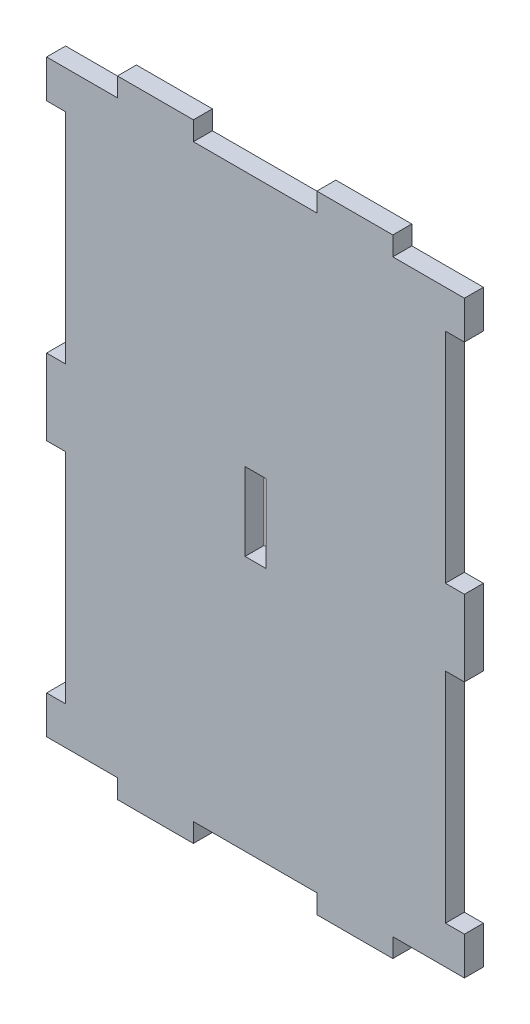
SolidWorks part; units mm, degrees
material "Plain Carbon Steel"
ref_plane "Front Plane" through (0, 0, 0) normal (0, 0, 1) x (1, 0, 0)
ref_plane "Top Plane" through (0, 0, 0) normal (0, 1, 0) x (1, 0, 0)
ref_plane "Right Plane" through (0, 0, 0) normal (1, 0, 0) x (0, 0, -1)
sketch "Model" plane through (0, 0, 0) normal (0, 0, 1) x (1, 0, 0)
  line L0 (-608.7043, -144.547) -> (-614.2043, -144.547)
  line L1 (-666.4543, -144.797) -> (-666.4543, -164.797)
  line L2 (-661.4543, -144.797) -> (-666.4543, -144.797)
  line L3 (-575.3026, -237.297) -> (-575.3026, -232.297)
  line L4 (-614.2043, -144.547) -> (-614.2043, -165.047)
  line L5 (-556.4543, -232.297) -> (-556.4543, -222.297)
  line L6 (-595.3026, -232.297) -> (-595.3026, -237.297)
  line L7 (-627.8026, -77.297) -> (-627.8026, -72.297)
  line L8 (-666.4543, -77.297) -> (-666.4543, -87.297)
  line L9 (-556.4543, -222.297) -> (-561.4543, -222.297)
  line L10 (-556.4543, -87.297) -> (-556.4543, -77.297)
  line L11 (-661.4543, -87.297) -> (-661.4543, -144.797)
  line L12 (-627.8026, -237.297) -> (-627.8026, -232.297)
  line L13 (-595.3026, -77.297) -> (-627.8026, -77.297)
  line L14 (-647.8026, -237.297) -> (-627.8026, -237.297)
  line L15 (-561.4543, -222.297) -> (-561.4543, -164.797)
  line L16 (-561.4543, -164.797) -> (-556.4543, -164.797)
  line L17 (-556.4543, -164.797) -> (-556.4543, -144.797)
  line L18 (-556.4543, -144.797) -> (-561.4543, -144.797)
  line L19 (-561.4543, -144.797) -> (-561.4543, -87.297)
  line L20 (-561.4543, -87.297) -> (-556.4543, -87.297)
  line L21 (-575.3026, -77.297) -> (-575.3026, -72.297)
  line L22 (-575.3026, -72.297) -> (-595.3026, -72.297)
  line L23 (-595.3026, -72.297) -> (-595.3026, -77.297)
  line L24 (-627.8026, -72.297) -> (-647.8026, -72.297)
  line L25 (-647.8026, -72.297) -> (-647.8026, -77.297)
  line L26 (-666.4543, -87.297) -> (-661.4543, -87.297)
  line L27 (-666.4543, -164.797) -> (-661.4543, -164.797)
  line L28 (-661.4543, -164.797) -> (-661.4543, -222.297)
  line L29 (-661.4543, -222.297) -> (-666.4543, -222.297)
  line L30 (-666.4543, -222.297) -> (-666.4543, -232.297)
  line L31 (-647.8026, -232.297) -> (-647.8026, -237.297)
  line L32 (-627.8026, -232.297) -> (-595.3026, -232.297)
  line L33 (-595.3026, -237.297) -> (-575.3026, -237.297)
  line L34 (-608.7043, -165.047) -> (-608.7043, -144.547)
  line L35 (-614.2043, -165.047) -> (-608.7043, -165.047)
  line L36 (-556.4543, -77.297) -> (-575.3026, -77.297)
  line L37 (-647.8026, -77.297) -> (-666.4543, -77.297)
  line L38 (-556.4543, -232.297) -> (-575.3026, -232.297)
  line L39 (-666.4543, -232.297) -> (-647.8026, -232.297)
  line L40 (-592.0745, -122.4427) -> (-592.0745, -123.504)
  line L41 (-594.1505, -124.5966) -> (-594.1505, -122.4427)
  line L42 (-594.1505, -122.4427) -> (-593.6198, -122.4427)
  line L43 (-584.9559, -123.4884) -> (-584.9559, -122.4427)
  line L44 (-593.1921, -123.504) -> (-592.0745, -123.504)
  line L45 (-594.6906, -122.4427) -> (-594.1505, -122.4427)
  line L46 (-593.1921, -123.504) -> (-593.1921, -122.4427)
  line L47 (-593.1921, -124.5966) -> (-593.1921, -123.504)
  line L48 (-591.6937, -124.5966) -> (-591.6937, -122.4396)
  line L49 (-591.1535, -124.4488) -> (-591.1836, -124.4044)
  line L50 (-591.1836, -124.4044) -> (-591.1937, -124.3563)
  line L51 (-590.0917, -123.5936) -> (-590.1732, -123.5033)
  line L52 (-591.1816, -123.2705) -> (-591.1453, -123.3191)
  line L53 (-590.8522, -124.5791) -> (-590.6317, -124.5966)
  line L54 (-591.1937, -124.3563) -> (-591.1937, -124.2033)
  line L55 (-590.1732, -123.5033) -> (-590.3079, -123.4484)
  line L56 (-591.0329, -124.5264) -> (-590.8522, -124.5791)
  line L57 (-590.0798, -122.635) -> (-590.11, -122.5906)
  line L58 (-591.1535, -124.4488) -> (-591.0329, -124.5264)
  line L59 (-590.4112, -122.4602) -> (-590.6317, -122.4427)
  line L60 (-591.1937, -123.2169) -> (-591.1816, -123.2705)
  line L61 (-591.1937, -122.6831) -> (-591.1836, -122.635)
  line L62 (-591.1453, -123.3191) -> (-591.0001, -123.401)
  line L63 (-591.1836, -122.635) -> (-591.1535, -122.5906)
  line L64 (-590.4959, -123.4291) -> (-590.3079, -123.4484)
  line L65 (-590.0917, -123.5936) -> (-590.0635, -123.7195)
  line L66 (-591.1937, -122.6831) -> (-591.1937, -123.2169)
  line L67 (-590.2305, -124.5264) -> (-590.4112, -124.5791)
  line L68 (-590.0635, -123.7195) -> (-590.0698, -124.3563)
  line L69 (-590.4112, -122.4602) -> (-590.2305, -122.5129)
  line L70 (-590.8522, -122.4602) -> (-590.6317, -122.4427)
  line L71 (-590.8366, -123.4205) -> (-590.4959, -123.4291)
  line L72 (-590.6317, -124.5966) -> (-590.4112, -124.5791)
  line L73 (-590.0798, -122.635) -> (-590.0698, -122.6831)
  line L74 (-591.0001, -123.401) -> (-590.8366, -123.4205)
  line L75 (-590.8522, -122.4602) -> (-591.0329, -122.5129)
  line L76 (-590.2305, -124.5264) -> (-590.11, -124.4488)
  line L77 (-590.11, -124.4488) -> (-590.0798, -124.4044)
  line L78 (-590.0798, -124.4044) -> (-590.0698, -124.3563)
  line L79 (-591.0329, -122.5129) -> (-591.1535, -122.5906)
  line L80 (-590.11, -122.5906) -> (-590.2305, -122.5129)
  line L81 (-590.0698, -122.836) -> (-590.0698, -122.6831)
  line L82 (-587.3259, -124.3563) -> (-587.3359, -124.4044)
  line L83 (-587.3359, -124.4044) -> (-587.3661, -124.4488)
  line L84 (-587.8878, -124.5966) -> (-588.1083, -124.5791)
  line L85 (-588.4397, -124.4044) -> (-588.4096, -124.4488)
  line L86 (-587.3478, -123.5936) -> (-587.4293, -123.5033)
  line L87 (-587.3661, -122.5906) -> (-587.3359, -122.635)
  line L88 (-588.4498, -124.3563) -> (-588.4397, -124.4044)
  line L89 (-587.3478, -123.5936) -> (-587.3196, -123.7195)
  line L90 (-588.4096, -122.5906) -> (-588.289, -122.5129)
  line L91 (-588.0927, -123.4205) -> (-588.2562, -123.401)
  line L92 (-588.4014, -123.3191) -> (-588.2562, -123.401)
  line L93 (-588.289, -124.5264) -> (-588.1083, -124.5791)
  line L94 (-587.3259, -124.3563) -> (-587.3196, -123.7195)
  line L95 (-587.752, -123.4291) -> (-587.564, -123.4484)
  line L96 (-587.6673, -124.5791) -> (-587.4866, -124.5264)
  line L97 (-587.752, -123.4291) -> (-588.0927, -123.4205)
  line L98 (-587.4866, -122.5129) -> (-587.6673, -122.4602)
  line L99 (-587.8878, -124.5966) -> (-587.6673, -124.5791)
  line L100 (-588.4498, -123.2169) -> (-588.4498, -122.6831)
  line L101 (-587.4293, -123.5033) -> (-587.564, -123.4484)
  line L102 (-588.4397, -122.635) -> (-588.4096, -122.5906)
  line L103 (-587.3259, -122.6831) -> (-587.3359, -122.635)
  line L104 (-588.4377, -123.2705) -> (-588.4498, -123.2169)
  line L105 (-587.4866, -124.5264) -> (-587.3661, -124.4488)
  line L106 (-588.4498, -122.6831) -> (-588.4397, -122.635)
  line L107 (-588.4096, -124.4488) -> (-588.289, -124.5264)
  line L108 (-587.3259, -122.836) -> (-587.3259, -122.6831)
  line L109 (-587.3661, -122.5906) -> (-587.4866, -122.5129)
  line L110 (-587.6673, -122.4602) -> (-587.8878, -122.4427)
  line L111 (-587.8878, -122.4427) -> (-588.1083, -122.4602)
  line L112 (-588.1083, -122.4602) -> (-588.289, -122.5129)
  line L113 (-588.4377, -123.2705) -> (-588.4014, -123.3191)
  line L114 (-581.0951, -124.4044) -> (-581.1252, -124.4488)
  line L115 (-583.8913, -122.4427) -> (-584.9559, -122.4427)
  line L116 (-579.5865, -124.3562) -> (-579.5865, -122.4518)
  line L117 (-585.5459, -122.5145) -> (-585.7285, -122.4606)
  line L118 (-586.4543, -122.4427) -> (-586.4543, -124.5966)
  line L119 (-585.3937, -122.6362) -> (-585.3835, -122.6831)
  line L120 (-585.4241, -122.5925) -> (-585.5459, -122.5145)
  line L121 (-584.9559, -124.5966) -> (-583.8913, -124.5966)
  line L122 (-585.5459, -124.528) -> (-585.7238, -124.5795)
  line L123 (-585.3937, -122.6362) -> (-585.4241, -122.5925)
  line L124 (-581.0951, -124.4044) -> (-581.085, -124.3563)
  line L125 (-585.4241, -124.4491) -> (-585.3937, -124.4045)
  line L126 (-584.9559, -124.5966) -> (-584.9559, -123.4884)
  line L127 (-585.5459, -124.528) -> (-585.4241, -124.4491)
  line L128 (-585.7238, -124.5795) -> (-585.9455, -124.5966)
  line L129 (-585.7285, -122.4606) -> (-585.9455, -122.4427)
  line L130 (-584.9559, -123.4884) -> (-584.0411, -123.4884)
  line L131 (-586.4543, -122.4427) -> (-585.9455, -122.4427)
  line L132 (-585.3937, -124.4045) -> (-585.3835, -124.3563)
  line L133 (-586.4543, -124.5966) -> (-585.9455, -124.5966)
  line L134 (-588.4498, -124.3563) -> (-588.4498, -124.2033)
  line L135 (-586.9543, -122.4396) -> (-586.9543, -124.5966)
  line L136 (-585.3835, -122.6831) -> (-585.3835, -124.3563)
  line L137 (-582.0481, -122.5129) -> (-581.8675, -122.4602)
  line L138 (-582.1989, -122.635) -> (-582.1687, -122.5906)
  line L139 (-582.1687, -122.5906) -> (-582.0481, -122.5129)
  line L140 (-581.8675, -122.4602) -> (-581.647, -122.4427)
  line L141 (-582.1989, -124.4044) -> (-582.2089, -124.3563)
  line L142 (-580.6702, -124.4487) -> (-580.7004, -124.4044)
  line L143 (-581.2458, -124.5264) -> (-581.4265, -124.5791)
  line L144 (-579.5966, -124.4044) -> (-579.5865, -124.3562)
  line L145 (-581.647, -122.4427) -> (-581.4265, -122.4602)
  line L146 (-582.1687, -124.4488) -> (-582.1989, -124.4044)
  line L147 (-581.2458, -122.5129) -> (-581.1252, -122.5906)
  line L148 (-582.0481, -124.5264) -> (-582.1687, -124.4488)
  line L149 (-582.2089, -122.6831) -> (-582.1989, -122.635)
  line L150 (-581.1252, -124.4488) -> (-581.2458, -124.5264)
  line L151 (-581.4265, -124.5791) -> (-581.647, -124.5966)
  line L152 (-580.7104, -124.3562) -> (-580.7104, -122.4518)
  line L153 (-579.5966, -124.4044) -> (-579.6267, -124.4487)
  line L154 (-580.7004, -124.4044) -> (-580.7104, -124.3562)
  line L155 (-592.0745, -123.504) -> (-592.0745, -124.5966)
  line L156 (-580.369, -124.5791) -> (-580.5497, -124.5264)
  line L157 (-579.212, -122.4427) -> (-578.6719, -122.4427)
  line L158 (-582.2089, -124.3563) -> (-582.2089, -122.6831)
  line L159 (-580.1485, -124.5966) -> (-579.928, -124.5791)
  line L160 (-581.8675, -124.5791) -> (-582.0481, -124.5264)
  line L161 (-581.4265, -122.4602) -> (-581.2458, -122.5129)
  line L162 (-578.6719, -124.5966) -> (-578.6719, -122.4427)
  line L163 (-581.647, -124.5966) -> (-581.8675, -124.5791)
  line L164 (-578.6719, -122.4427) -> (-578.1411, -122.4427)
  line L165 (-580.1485, -124.5966) -> (-580.369, -124.5791)
  line L166 (-581.1252, -122.5906) -> (-581.0951, -122.635)
  line L167 (-581.0951, -122.635) -> (-581.085, -122.6831)
  line L168 (-579.6267, -124.4487) -> (-579.7473, -124.5264)
  line L169 (-581.085, -122.6831) -> (-581.085, -124.3563)
  line L170 (-580.6702, -124.4487) -> (-580.5497, -124.5264)
  line L171 (-579.928, -124.5791) -> (-579.7473, -124.5264)
  line L172 (-590.5032, -119.8589) -> (-590.9996, -120.168)
  line L173 (-594.6211, -111.8268) -> (-594.6211, -116.047)
  line L174 (-594.6211, -120.4427) -> (-592.5856, -120.4427)
  line L175 (-591.7208, -120.374) -> (-592.5856, -120.4427)
  line L176 (-585.2055, -116.7973) -> (-586.5043, -111.8146)
  line L177 (-590.3791, -119.6786) -> (-590.5032, -119.8589)
  line L178 (-590.9996, -120.168) -> (-591.7208, -120.374)
  line L179 (-590.3378, -119.4812) -> (-590.3791, -119.6786)
  line L180 (-587.7281, -116.7973) -> (-588.6272, -120.4427)
  line L181 (-582.6333, -119.4812) -> (-582.5931, -119.6736)
  line L182 (-590.3378, -115.1236) -> (-590.3378, -112.7884)
  line L183 (-591.4711, -116.1843) -> (-592.5856, -116.047)
  line L184 (-584.2565, -120.4427) -> (-585.2055, -116.7973)
  line L185 (-590.4533, -115.4327) -> (-590.3378, -115.1236)
  line L186 (-590.4533, -116.6651) -> (-590.7999, -116.3967)
  line L187 (-590.7999, -116.3967) -> (-591.4711, -116.1843)
  line L188 (-581.9902, -120.1617) -> (-581.2675, -120.3724)
  line L189 (-580.3855, -120.4427) -> (-581.2675, -120.3724)
  line L190 (-590.3378, -119.4812) -> (-590.3378, -116.9711)
  line L191 (-590.3378, -116.9711) -> (-590.4533, -116.6651)
  line L192 (-578.2876, -111.8268) -> (-582.6333, -111.8268)
  line L193 (-591.7271, -111.8986) -> (-592.5856, -111.8268)
  line L194 (-594.6211, -111.8268) -> (-592.5856, -111.8268)
  line L195 (-582.6333, -111.8268) -> (-582.6333, -116.0599)
  line L196 (-590.4533, -115.4327) -> (-590.7999, -115.7102)
  line L197 (-586.5043, -111.8146) -> (-587.7281, -116.7973)
  line L198 (-582.4725, -119.8511) -> (-582.5931, -119.6736)
  line L199 (-590.5032, -112.4263) -> (-590.9996, -112.114)
  line L200 (-592.5856, -116.047) -> (-594.6211, -116.047)
  line L201 (-587.7281, -116.7973) -> (-585.2055, -116.7973)
  line L202 (-582.4725, -119.8511) -> (-581.9902, -120.1617)
  line L203 (-590.7999, -115.7102) -> (-591.4836, -115.9194)
  line L204 (-590.3791, -112.601) -> (-590.5032, -112.4263)
  line L205 (-591.7271, -111.8986) -> (-590.9996, -112.114)
  line L206 (-592.5856, -116.047) -> (-591.4836, -115.9194)
  line L207 (-590.3791, -112.601) -> (-590.3378, -112.7884)
  line L208 (-578.7808, -120.1617) -> (-579.5035, -120.3724)
  line L209 (-580.3855, -115.0983) -> (-579.5035, -115.1685)
  line L210 (-579.5035, -120.3724) -> (-580.3855, -120.4427)
  line L211 (-578.7808, -115.3792) -> (-578.2985, -115.6899)
  line L212 (-578.1779, -119.6736) -> (-578.2985, -119.8511)
  line L213 (-578.1377, -119.4812) -> (-578.1779, -119.6736)
  line L214 (-582.1963, -115.551) -> (-581.7342, -115.2981)
  line L215 (-578.2985, -115.6899) -> (-578.1779, -115.8675)
  line L216 (-578.1779, -115.8675) -> (-578.1377, -116.0599)
  line L217 (-579.5035, -115.1685) -> (-578.7808, -115.3792)
  line L218 (-578.2985, -119.8511) -> (-578.7808, -120.1617)
  line L219 (-594.6211, -116.047) -> (-594.6211, -120.4427)
  line L220 (-581.7342, -115.2981) -> (-580.3855, -115.0983)
  line L221 (-582.6333, -116.0599) -> (-582.1963, -115.551)
  line L222 (-578.1377, -116.0599) -> (-578.1377, -119.4812)
  line L223 (-594.6211, -121.4427) -> (-578.2876, -121.4427)
  line L224 (-659.4543, -82.297) -> (-664.4543, -82.297)
  line L225 (-662.4543, -81.297) -> (-664.4543, -82.297)
  line L226 (-662.4543, -83.297) -> (-664.4543, -82.297)
  line L227 (-656.9543, -84.4948) -> (-656.9543, -82.297)
  line L228 (-656.9543, -82.297) -> (-655.9366, -82.297)
  line L229 (-655.9366, -82.297) -> (-655.3793, -82.3657)
  line L230 (-655.3793, -82.3657) -> (-655.0437, -82.4718)
  line L231 (-655.0437, -82.4718) -> (-654.8704, -82.6061)
  line L232 (-654.8704, -82.6061) -> (-654.8127, -82.759)
  line L233 (-654.8127, -82.759) -> (-654.8127, -84.014)
  line L234 (-654.8127, -84.014) -> (-654.8334, -84.1128)
  line L235 (-654.8334, -84.1128) -> (-654.8954, -84.2029)
  line L236 (-654.8954, -84.2029) -> (-655.1436, -84.3575)
  line L237 (-655.1436, -84.3575) -> (-655.5042, -84.4605)
  line L238 (-655.5042, -84.4605) -> (-655.9366, -84.4948)
  line L239 (-655.9366, -84.4948) -> (-656.9543, -84.4948)
  line L240 (-656.9543, -80.1869) -> (-656.9543, -84.4948)
  line L241 (-656.9543, -84.4948) -> (-655.9366, -84.4948)
  line L242 (-655.9366, -84.4948) -> (-655.5042, -84.4605)
  line L243 (-655.5042, -84.4605) -> (-655.1436, -84.3575)
  line L244 (-655.1436, -84.3575) -> (-654.8954, -84.203)
  line L245 (-654.8954, -84.203) -> (-654.8334, -84.1128)
  line L246 (-654.8334, -84.1128) -> (-654.8127, -84.0141)
  line L247 (-654.8127, -84.0141) -> (-654.8127, -82.7592)
  line L248 (-654.8127, -82.7592) -> (-654.8704, -82.6062)
  line L249 (-654.8704, -82.6062) -> (-655.0437, -82.472)
  line L250 (-655.0437, -82.472) -> (-655.3793, -82.3659)
  line L251 (-655.3793, -82.3659) -> (-655.9366, -82.2972)
  line L252 (-655.9366, -82.2972) -> (-655.3856, -82.2332)
  line L253 (-655.3856, -82.2332) -> (-655.0437, -82.1286)
  line L254 (-655.0437, -82.1286) -> (-654.8704, -81.9897)
  line L255 (-654.8704, -81.9897) -> (-654.8127, -81.8352)
  line L256 (-654.8127, -81.8352) -> (-654.8127, -80.6677)
  line L257 (-654.8127, -80.6677) -> (-654.8334, -80.574)
  line L258 (-654.8334, -80.574) -> (-654.8954, -80.4866)
  line L259 (-654.8954, -80.4866) -> (-655.1436, -80.3305)
  line L260 (-655.1436, -80.3305) -> (-655.5073, -80.2228)
  line L261 (-655.5073, -80.2228) -> (-655.9366, -80.1869)
  line L262 (-655.9366, -80.1869) -> (-656.9543, -80.1869)
  line L263 (-655.9366, -82.2974) -> (-656.9543, -82.2974)
  line L264 (-656.9543, -82.2974) -> (-656.9543, -80.1869)
  line L265 (-656.9543, -80.1869) -> (-655.9366, -80.1869)
  line L266 (-655.9366, -80.1869) -> (-655.5073, -80.2228)
  line L267 (-655.5073, -80.2228) -> (-655.1436, -80.3305)
  line L268 (-655.1436, -80.3305) -> (-654.8954, -80.4867)
  line L269 (-654.8954, -80.4867) -> (-654.8334, -80.5741)
  line L270 (-654.8334, -80.5741) -> (-654.8127, -80.6677)
  line L271 (-654.8127, -80.6677) -> (-654.8127, -81.8353)
  line L272 (-654.8127, -81.8353) -> (-654.8704, -81.9899)
  line L273 (-654.8704, -81.9899) -> (-655.0437, -82.1288)
  line L274 (-655.0437, -82.1288) -> (-655.3856, -82.2334)
  line L275 (-655.3856, -82.2334) -> (-655.9366, -82.2974)
  line L276 (-653.9574, -84.4948) -> (-653.9574, -80.1869)
  line L277 (-653.9574, -80.1869) -> (-652.9396, -80.1869)
  line L278 (-652.9396, -80.1869) -> (-652.5057, -80.2228)
  line L279 (-652.5057, -80.2228) -> (-652.1404, -80.3305)
  line L280 (-652.1404, -80.3305) -> (-651.8969, -80.4866)
  line L281 (-651.8969, -80.4866) -> (-651.836, -80.574)
  line L282 (-651.836, -80.574) -> (-651.8157, -80.6677)
  line L283 (-651.8157, -80.6677) -> (-651.8157, -84.0141)
  line L284 (-651.8157, -84.0141) -> (-651.836, -84.1105)
  line L285 (-651.836, -84.1105) -> (-651.8969, -84.1998)
  line L286 (-651.8969, -84.1998) -> (-652.1404, -84.3575)
  line L287 (-652.1404, -84.3575) -> (-652.4963, -84.4605)
  line L288 (-652.4963, -84.4605) -> (-652.9396, -84.4948)
  line L289 (-652.9396, -84.4948) -> (-653.9574, -84.4948)
  line L290 (-653.9574, -80.1869) -> (-653.9574, -84.4948)
  line L291 (-653.9574, -84.4948) -> (-652.9396, -84.4948)
  line L292 (-652.9396, -84.4948) -> (-652.4963, -84.4605)
  line L293 (-652.4963, -84.4605) -> (-652.1404, -84.3575)
  line L294 (-652.1404, -84.3575) -> (-651.8969, -84.1998)
  line L295 (-651.8969, -84.1998) -> (-651.836, -84.1105)
  line L296 (-651.836, -84.1105) -> (-651.8157, -84.0141)
  line L297 (-651.8157, -84.0141) -> (-651.8157, -80.6677)
  line L298 (-651.8157, -80.6677) -> (-651.836, -80.574)
  line L299 (-651.836, -80.574) -> (-651.8969, -80.4866)
  line L300 (-651.8969, -80.4866) -> (-652.1404, -80.3305)
  line L301 (-652.1404, -80.3305) -> (-652.5057, -80.2228)
  line L302 (-652.5057, -80.2228) -> (-652.9396, -80.1869)
  line L303 (-652.9396, -80.1869) -> (-653.9574, -80.1869)
  line L304 (-650.2775, -84.4597) -> (-650.6389, -84.3544)
  line L305 (-650.6389, -84.3544) -> (-650.8801, -84.1991)
  line L306 (-650.8801, -84.1991) -> (-650.9403, -84.1103)
  line L307 (-650.9403, -84.1103) -> (-650.9604, -84.0141)
  line L308 (-650.9604, -84.0141) -> (-650.9403, -84.1103)
  line L309 (-650.9403, -84.1103) -> (-650.8801, -84.1991)
  line L310 (-650.8801, -84.1991) -> (-650.6389, -84.3544)
  line L311 (-650.6389, -84.3544) -> (-650.2775, -84.4597)
  line L312 (-649.3955, -84.4597) -> (-649.0342, -84.3544)
  line L313 (-649.0342, -84.3544) -> (-648.793, -84.1991)
  line L314 (-648.793, -84.1991) -> (-648.7327, -84.1103)
  line L315 (-648.7327, -84.1103) -> (-648.7126, -84.0141)
  line L316 (-648.7126, -84.0141) -> (-648.7126, -82.3034)
  line L317 (-648.7126, -82.3034) -> (-648.7327, -82.2072)
  line L318 (-648.7327, -82.2072) -> (-648.793, -82.1184)
  line L319 (-648.793, -82.1184) -> (-649.0342, -81.9631)
  line L320 (-649.0342, -81.9631) -> (-649.3955, -81.8578)
  line L321 (-649.3955, -81.8578) -> (-649.8365, -81.8226)
  line L322 (-649.8365, -81.8226) -> (-650.5109, -81.9226)
  line L323 (-650.5109, -81.9226) -> (-650.7419, -82.049)
  line L324 (-650.7419, -82.049) -> (-650.9604, -82.3034)
  line L325 (-650.9604, -82.3034) -> (-650.9604, -80.1869)
  line L326 (-650.9604, -80.1869) -> (-648.7876, -80.1869)
  line L327 (-648.7876, -80.1869) -> (-650.9604, -80.1869)
  line L328 (-650.9604, -80.1869) -> (-650.9604, -82.3034)
  line L329 (-650.9604, -82.3034) -> (-650.7419, -82.049)
  line L330 (-650.7419, -82.049) -> (-650.5109, -81.9226)
  line L331 (-650.5109, -81.9226) -> (-649.8365, -81.8226)
  line L332 (-649.8365, -81.8226) -> (-649.3955, -81.8578)
  line L333 (-649.3955, -81.8578) -> (-649.0342, -81.9631)
  line L334 (-649.0342, -81.9631) -> (-648.793, -82.1184)
  line L335 (-648.793, -82.1184) -> (-648.7327, -82.2072)
  line L336 (-648.7327, -82.2072) -> (-648.7126, -82.3034)
  line L337 (-648.7126, -82.3034) -> (-648.7126, -84.0141)
  line L338 (-648.7126, -84.0141) -> (-648.7327, -84.1103)
  line L339 (-648.7327, -84.1103) -> (-648.793, -84.1991)
  line L340 (-648.793, -84.1991) -> (-649.0342, -84.3544)
  line L341 (-649.0342, -84.3544) -> (-649.3955, -84.4597)
  line L342 (-649.3955, -84.4597) -> (-649.8365, -84.4948)
  line L343 (-649.8365, -84.4948) -> (-650.2775, -84.4597)
  line L344 (-563.4543, -227.297) -> (-558.4543, -227.297)
  line L345 (-560.4543, -228.297) -> (-558.4543, -227.297)
  line L346 (-560.4543, -226.297) -> (-558.4543, -227.297)
  line L347 (-574.1961, -229.4071) -> (-574.1961, -227.2093)
  line L348 (-574.1961, -227.2093) -> (-573.1783, -227.2093)
  line L349 (-573.1783, -227.2093) -> (-572.621, -227.2779)
  line L350 (-572.621, -227.2779) -> (-572.2854, -227.3841)
  line L351 (-572.2854, -227.3841) -> (-572.1121, -227.5183)
  line L352 (-572.1121, -227.5183) -> (-572.0544, -227.6713)
  line L353 (-572.0544, -227.6713) -> (-572.0544, -228.9263)
  line L354 (-572.0544, -228.9263) -> (-572.0751, -229.025)
  line L355 (-572.0751, -229.025) -> (-572.1371, -229.1152)
  line L356 (-572.1371, -229.1152) -> (-572.3853, -229.2697)
  line L357 (-572.3853, -229.2697) -> (-572.7459, -229.3728)
  line L358 (-572.7459, -229.3728) -> (-573.1783, -229.4071)
  line L359 (-573.1783, -229.4071) -> (-574.1961, -229.4071)
  line L360 (-574.1961, -225.0992) -> (-574.1961, -229.4071)
  line L361 (-574.1961, -229.4071) -> (-573.1783, -229.4071)
  line L362 (-573.1783, -229.4071) -> (-572.7459, -229.3728)
  line L363 (-572.7459, -229.3728) -> (-572.3853, -229.2698)
  line L364 (-572.3853, -229.2698) -> (-572.1371, -229.1152)
  line L365 (-572.1371, -229.1152) -> (-572.0751, -229.0251)
  line L366 (-572.0751, -229.0251) -> (-572.0544, -228.9263)
  line L367 (-572.0544, -228.9263) -> (-572.0544, -227.6714)
  line L368 (-572.0544, -227.6714) -> (-572.1121, -227.5185)
  line L369 (-572.1121, -227.5185) -> (-572.2854, -227.3843)
  line L370 (-572.2854, -227.3843) -> (-572.621, -227.2781)
  line L371 (-572.621, -227.2781) -> (-573.1783, -227.2095)
  line L372 (-573.1783, -227.2095) -> (-572.6273, -227.1455)
  line L373 (-572.6273, -227.1455) -> (-572.2854, -227.0409)
  line L374 (-572.2854, -227.0409) -> (-572.1121, -226.902)
  line L375 (-572.1121, -226.902) -> (-572.0544, -226.7474)
  line L376 (-572.0544, -226.7474) -> (-572.0544, -225.5799)
  line L377 (-572.0544, -225.5799) -> (-572.0751, -225.4863)
  line L378 (-572.0751, -225.4863) -> (-572.1371, -225.3989)
  line L379 (-572.1371, -225.3989) -> (-572.3853, -225.2427)
  line L380 (-572.3853, -225.2427) -> (-572.749, -225.1351)
  line L381 (-572.749, -225.1351) -> (-573.1783, -225.0992)
  line L382 (-573.1783, -225.0992) -> (-574.1961, -225.0992)
  line L383 (-573.1783, -227.2096) -> (-574.1961, -227.2096)
  line L384 (-574.1961, -227.2096) -> (-574.1961, -225.0992)
  line L385 (-574.1961, -225.0992) -> (-573.1783, -225.0992)
  line L386 (-573.1783, -225.0992) -> (-572.749, -225.1351)
  line L387 (-572.749, -225.1351) -> (-572.3853, -225.2428)
  line L388 (-572.3853, -225.2428) -> (-572.1371, -225.3989)
  line L389 (-572.1371, -225.3989) -> (-572.0751, -225.4863)
  line L390 (-572.0751, -225.4863) -> (-572.0544, -225.58)
  line L391 (-572.0544, -225.58) -> (-572.0544, -226.7476)
  line L392 (-572.0544, -226.7476) -> (-572.1121, -226.9021)
  line L393 (-572.1121, -226.9021) -> (-572.2854, -227.0411)
  line L394 (-572.2854, -227.0411) -> (-572.6273, -227.1456)
  line L395 (-572.6273, -227.1456) -> (-573.1783, -227.2096)
  line L396 (-571.1991, -229.4071) -> (-571.1991, -225.0992)
  line L397 (-571.1991, -225.0992) -> (-570.1813, -225.0992)
  line L398 (-570.1813, -225.0992) -> (-569.7474, -225.1351)
  line L399 (-569.7474, -225.1351) -> (-569.3821, -225.2427)
  line L400 (-569.3821, -225.2427) -> (-569.1386, -225.3989)
  line L401 (-569.1386, -225.3989) -> (-569.0777, -225.4863)
  line L402 (-569.0777, -225.4863) -> (-569.0574, -225.5799)
  line L403 (-569.0574, -225.5799) -> (-569.0574, -228.9263)
  line L404 (-569.0574, -228.9263) -> (-569.0777, -229.0227)
  line L405 (-569.0777, -229.0227) -> (-569.1386, -229.1121)
  line L406 (-569.1386, -229.1121) -> (-569.3821, -229.2698)
  line L407 (-569.3821, -229.2698) -> (-569.738, -229.3728)
  line L408 (-569.738, -229.3728) -> (-570.1813, -229.4071)
  line L409 (-570.1813, -229.4071) -> (-571.1991, -229.4071)
  line L410 (-571.1991, -225.0992) -> (-571.1991, -229.4071)
  line L411 (-571.1991, -229.4071) -> (-570.1813, -229.4071)
  line L412 (-570.1813, -229.4071) -> (-569.738, -229.3728)
  line L413 (-569.738, -229.3728) -> (-569.3821, -229.2698)
  line L414 (-569.3821, -229.2698) -> (-569.1386, -229.1121)
  line L415 (-569.1386, -229.1121) -> (-569.0777, -229.0227)
  line L416 (-569.0777, -229.0227) -> (-569.0574, -228.9263)
  line L417 (-569.0574, -228.9263) -> (-569.0574, -225.5799)
  line L418 (-569.0574, -225.5799) -> (-569.0777, -225.4863)
  line L419 (-569.0777, -225.4863) -> (-569.1386, -225.3989)
  line L420 (-569.1386, -225.3989) -> (-569.3821, -225.2427)
  line L421 (-569.3821, -225.2427) -> (-569.7474, -225.1351)
  line L422 (-569.7474, -225.1351) -> (-570.1813, -225.0992)
  line L423 (-570.1813, -225.0992) -> (-571.1991, -225.0992)
  line L424 (-567.5192, -229.372) -> (-567.8806, -229.2666)
  line L425 (-567.8806, -229.2666) -> (-568.1218, -229.1113)
  line L426 (-568.1218, -229.1113) -> (-568.1821, -229.0225)
  line L427 (-568.1821, -229.0225) -> (-568.2021, -228.9263)
  line L428 (-568.2021, -228.9263) -> (-568.1821, -229.0225)
  line L429 (-568.1821, -229.0225) -> (-568.1218, -229.1113)
  line L430 (-568.1218, -229.1113) -> (-567.8806, -229.2666)
  line L431 (-567.8806, -229.2666) -> (-567.5192, -229.372)
  line L432 (-566.6373, -229.372) -> (-566.2759, -229.2666)
  line L433 (-566.2759, -229.2666) -> (-566.0347, -229.1113)
  line L434 (-566.0347, -229.1113) -> (-565.9744, -229.0225)
  line L435 (-565.9744, -229.0225) -> (-565.9543, -228.9263)
  line L436 (-565.9543, -228.9263) -> (-565.9543, -227.2157)
  line L437 (-565.9543, -227.2157) -> (-565.9744, -227.1195)
  line L438 (-565.9744, -227.1195) -> (-566.0347, -227.0307)
  line L439 (-566.0347, -227.0307) -> (-566.2759, -226.8754)
  line L440 (-566.2759, -226.8754) -> (-566.6373, -226.77)
  line L441 (-566.6373, -226.77) -> (-567.0782, -226.7349)
  line L442 (-567.0782, -226.7349) -> (-567.7526, -226.8348)
  line L443 (-567.7526, -226.8348) -> (-567.9836, -226.9612)
  line L444 (-567.9836, -226.9612) -> (-568.2021, -227.2157)
  line L445 (-568.2021, -227.2157) -> (-568.2021, -225.0992)
  line L446 (-568.2021, -225.0992) -> (-566.0293, -225.0992)
  line L447 (-566.0293, -225.0992) -> (-568.2021, -225.0992)
  line L448 (-568.2021, -225.0992) -> (-568.2021, -227.2157)
  line L449 (-568.2021, -227.2157) -> (-567.9836, -226.9612)
  line L450 (-567.9836, -226.9612) -> (-567.7526, -226.8348)
  line L451 (-567.7526, -226.8348) -> (-567.0782, -226.7349)
  line L452 (-567.0782, -226.7349) -> (-566.6373, -226.77)
  line L453 (-566.6373, -226.77) -> (-566.2759, -226.8754)
  line L454 (-566.2759, -226.8754) -> (-566.0347, -227.0307)
  line L455 (-566.0347, -227.0307) -> (-565.9744, -227.1195)
  line L456 (-565.9744, -227.1195) -> (-565.9543, -227.2157)
  line L457 (-565.9543, -227.2157) -> (-565.9543, -228.9263)
  line L458 (-565.9543, -228.9263) -> (-565.9744, -229.0225)
  line L459 (-565.9744, -229.0225) -> (-566.0347, -229.1113)
  line L460 (-566.0347, -229.1113) -> (-566.2759, -229.2666)
  line L461 (-566.2759, -229.2666) -> (-566.6373, -229.372)
  line L462 (-566.6373, -229.372) -> (-567.0782, -229.4071)
  line L463 (-567.0782, -229.4071) -> (-567.5192, -229.372)
  line L464 (-588.425, -84.6049) -> (-588.425, -82.4071)
  line L465 (-588.425, -82.4071) -> (-587.4072, -82.4071)
  line L466 (-587.4072, -82.4071) -> (-586.85, -82.4758)
  line L467 (-586.85, -82.4758) -> (-586.5143, -82.5819)
  line L468 (-586.5143, -82.5819) -> (-586.3411, -82.7162)
  line L469 (-586.3411, -82.7162) -> (-586.2833, -82.8691)
  line L470 (-586.2833, -82.8691) -> (-586.2833, -84.1241)
  line L471 (-586.2833, -84.1241) -> (-586.304, -84.2229)
  line L472 (-586.304, -84.2229) -> (-586.366, -84.313)
  line L473 (-586.366, -84.313) -> (-586.6142, -84.4675)
  line L474 (-586.6142, -84.4675) -> (-586.9748, -84.5706)
  line L475 (-586.9748, -84.5706) -> (-587.4072, -84.6049)
  line L476 (-587.4072, -84.6049) -> (-588.425, -84.6049)
  line L477 (-588.425, -80.297) -> (-588.425, -84.6049)
  line L478 (-588.425, -84.6049) -> (-587.4072, -84.6049)
  line L479 (-587.4072, -84.6049) -> (-586.9748, -84.5706)
  line L480 (-586.9748, -84.5706) -> (-586.6142, -84.4676)
  line L481 (-586.6142, -84.4676) -> (-586.366, -84.3131)
  line L482 (-586.366, -84.3131) -> (-586.304, -84.2229)
  line L483 (-586.304, -84.2229) -> (-586.2833, -84.1242)
  line L484 (-586.2833, -84.1242) -> (-586.2833, -82.8693)
  line L485 (-586.2833, -82.8693) -> (-586.3411, -82.7163)
  line L486 (-586.3411, -82.7163) -> (-586.5143, -82.5821)
  line L487 (-586.5143, -82.5821) -> (-586.85, -82.476)
  line L488 (-586.85, -82.476) -> (-587.4072, -82.4073)
  line L489 (-587.4072, -82.4073) -> (-586.8562, -82.3433)
  line L490 (-586.8562, -82.3433) -> (-586.5143, -82.2387)
  line L491 (-586.5143, -82.2387) -> (-586.3411, -82.0998)
  line L492 (-586.3411, -82.0998) -> (-586.2833, -81.9453)
  line L493 (-586.2833, -81.9453) -> (-586.2833, -80.7778)
  line L494 (-586.2833, -80.7778) -> (-586.304, -80.6841)
  line L495 (-586.304, -80.6841) -> (-586.366, -80.5967)
  line L496 (-586.366, -80.5967) -> (-586.6142, -80.4406)
  line L497 (-586.6142, -80.4406) -> (-586.978, -80.3329)
  line L498 (-586.978, -80.3329) -> (-587.4072, -80.297)
  line L499 (-587.4072, -80.297) -> (-588.425, -80.297)
  line L500 (-587.4072, -82.4075) -> (-588.425, -82.4075)
  line L501 (-588.425, -82.4075) -> (-588.425, -80.297)
  line L502 (-588.425, -80.297) -> (-587.4072, -80.297)
  line L503 (-587.4072, -80.297) -> (-586.978, -80.3329)
  line L504 (-586.978, -80.3329) -> (-586.6142, -80.4406)
  line L505 (-586.6142, -80.4406) -> (-586.366, -80.5967)
  line L506 (-586.366, -80.5967) -> (-586.304, -80.6842)
  line L507 (-586.304, -80.6842) -> (-586.2833, -80.7778)
  line L508 (-586.2833, -80.7778) -> (-586.2833, -81.9454)
  line L509 (-586.2833, -81.9454) -> (-586.3411, -82.0999)
  line L510 (-586.3411, -82.0999) -> (-586.5143, -82.2389)
  line L511 (-586.5143, -82.2389) -> (-586.8562, -82.3435)
  line L512 (-586.8562, -82.3435) -> (-587.4072, -82.4075)
  line L513 (-585.428, -80.2909) -> (-585.428, -84.6049)
  line L514 (-583.3041, -84.6049) -> (-583.7451, -84.5698)
  line L515 (-583.7451, -84.5698) -> (-584.1065, -84.4645)
  line L516 (-584.1065, -84.4645) -> (-584.3476, -84.3091)
  line L517 (-584.3476, -84.3091) -> (-584.4079, -84.2204)
  line L518 (-584.4079, -84.2204) -> (-584.428, -84.1242)
  line L519 (-584.428, -84.1242) -> (-584.4079, -84.2204)
  line L520 (-584.4079, -84.2204) -> (-584.3476, -84.3091)
  line L521 (-584.3476, -84.3091) -> (-584.1065, -84.4645)
  line L522 (-584.1065, -84.4645) -> (-583.7451, -84.5698)
  line L523 (-582.8631, -84.5698) -> (-582.5018, -84.4645)
  line L524 (-582.5018, -84.4645) -> (-582.2606, -84.3091)
  line L525 (-582.2606, -84.3091) -> (-582.2003, -84.2204)
  line L526 (-582.2003, -84.2204) -> (-582.1802, -84.1242)
  line L527 (-582.1802, -84.1242) -> (-582.1802, -82.4135)
  line L528 (-582.1802, -82.4135) -> (-582.2003, -82.3173)
  line L529 (-582.2003, -82.3173) -> (-582.2606, -82.2285)
  line L530 (-582.2606, -82.2285) -> (-582.5018, -82.0732)
  line L531 (-582.5018, -82.0732) -> (-582.8631, -81.9678)
  line L532 (-582.8631, -81.9678) -> (-583.3041, -81.9327)
  line L533 (-583.3041, -81.9327) -> (-583.9785, -82.0326)
  line L534 (-583.9785, -82.0326) -> (-584.2095, -82.1591)
  line L535 (-584.2095, -82.1591) -> (-584.428, -82.4135)
  line L536 (-584.428, -82.4135) -> (-584.428, -80.297)
  line L537 (-584.428, -80.297) -> (-582.2552, -80.297)
  line L538 (-582.2552, -80.297) -> (-584.428, -80.297)
  line L539 (-584.428, -80.297) -> (-584.428, -82.4135)
  line L540 (-584.428, -82.4135) -> (-584.2095, -82.1591)
  line L541 (-584.2095, -82.1591) -> (-583.9785, -82.0326)
  line L542 (-583.9785, -82.0326) -> (-583.3041, -81.9327)
  line L543 (-583.3041, -81.9327) -> (-582.8631, -81.9678)
  line L544 (-582.8631, -81.9678) -> (-582.5018, -82.0732)
  line L545 (-582.5018, -82.0732) -> (-582.2606, -82.2285)
  line L546 (-582.2606, -82.2285) -> (-582.2003, -82.3173)
  line L547 (-582.2003, -82.3173) -> (-582.1802, -82.4135)
  line L548 (-582.1802, -82.4135) -> (-582.1802, -84.1242)
  line L549 (-582.1802, -84.1242) -> (-582.2003, -84.2204)
  line L550 (-582.2003, -84.2204) -> (-582.2606, -84.3091)
  line L551 (-582.2606, -84.3091) -> (-582.5018, -84.4645)
  line L552 (-582.5018, -84.4645) -> (-582.8631, -84.5698)
  line L553 (-582.8631, -84.5698) -> (-583.3041, -84.6049)
  line L554 (-585.3026, -79.297) -> (-585.3026, -74.297)
  line L555 (-584.3026, -76.297) -> (-585.3026, -74.297)
  line L556 (-586.3026, -76.297) -> (-585.3026, -74.297)
  line L557 (-641.9235, -229.297) -> (-641.9235, -227.0992)
  line L558 (-641.9235, -227.0992) -> (-640.9057, -227.0992)
  line L559 (-640.9057, -227.0992) -> (-640.3485, -227.1678)
  line L560 (-640.3485, -227.1678) -> (-640.0129, -227.274)
  line L561 (-640.0129, -227.274) -> (-639.8396, -227.4082)
  line L562 (-639.8396, -227.4082) -> (-639.7818, -227.5612)
  line L563 (-639.7818, -227.5612) -> (-639.7818, -228.8162)
  line L564 (-639.7818, -228.8162) -> (-639.8025, -228.9149)
  line L565 (-639.8025, -228.9149) -> (-639.8645, -229.0051)
  line L566 (-639.8645, -229.0051) -> (-640.1128, -229.1596)
  line L567 (-640.1128, -229.1596) -> (-640.4733, -229.2627)
  line L568 (-640.4733, -229.2627) -> (-640.9057, -229.297)
  line L569 (-640.9057, -229.297) -> (-641.9235, -229.297)
  line L570 (-641.9235, -224.9891) -> (-641.9235, -229.297)
  line L571 (-641.9235, -229.297) -> (-640.9057, -229.297)
  line L572 (-640.9057, -229.297) -> (-640.4733, -229.2627)
  line L573 (-640.4733, -229.2627) -> (-640.1128, -229.1597)
  line L574 (-640.1128, -229.1597) -> (-639.8645, -229.0051)
  line L575 (-639.8645, -229.0051) -> (-639.8025, -228.915)
  line L576 (-639.8025, -228.915) -> (-639.7818, -228.8163)
  line L577 (-639.7818, -228.8163) -> (-639.7818, -227.5613)
  line L578 (-639.7818, -227.5613) -> (-639.8396, -227.4084)
  line L579 (-639.8396, -227.4084) -> (-640.0129, -227.2742)
  line L580 (-640.0129, -227.2742) -> (-640.3485, -227.168)
  line L581 (-640.3485, -227.168) -> (-640.9057, -227.0994)
  line L582 (-640.9057, -227.0994) -> (-640.3547, -227.0354)
  line L583 (-640.3547, -227.0354) -> (-640.0129, -226.9308)
  line L584 (-640.0129, -226.9308) -> (-639.8396, -226.7919)
  line L585 (-639.8396, -226.7919) -> (-639.7818, -226.6373)
  line L586 (-639.7818, -226.6373) -> (-639.7818, -225.4698)
  line L587 (-639.7818, -225.4698) -> (-639.8025, -225.3762)
  line L588 (-639.8025, -225.3762) -> (-639.8645, -225.2888)
  line L589 (-639.8645, -225.2888) -> (-640.1128, -225.1327)
  line L590 (-640.1128, -225.1327) -> (-640.4765, -225.025)
  line L591 (-640.4765, -225.025) -> (-640.9057, -224.9891)
  line L592 (-640.9057, -224.9891) -> (-641.9235, -224.9891)
  line L593 (-640.9057, -227.0996) -> (-641.9235, -227.0996)
  line L594 (-641.9235, -227.0996) -> (-641.9235, -224.9891)
  line L595 (-641.9235, -224.9891) -> (-640.9057, -224.9891)
  line L596 (-640.9057, -224.9891) -> (-640.4765, -225.025)
  line L597 (-640.4765, -225.025) -> (-640.1128, -225.1327)
  line L598 (-640.1128, -225.1327) -> (-639.8645, -225.2888)
  line L599 (-639.8645, -225.2888) -> (-639.8025, -225.3762)
  line L600 (-639.8025, -225.3762) -> (-639.7818, -225.4699)
  line L601 (-639.7818, -225.4699) -> (-639.7818, -226.6375)
  line L602 (-639.7818, -226.6375) -> (-639.8396, -226.792)
  line L603 (-639.8396, -226.792) -> (-640.0129, -226.931)
  line L604 (-640.0129, -226.931) -> (-640.3547, -227.0355)
  line L605 (-640.3547, -227.0355) -> (-640.9057, -227.0996)
  line L606 (-636.6787, -228.8163) -> (-636.6988, -228.9124)
  line L607 (-636.6988, -228.9124) -> (-636.7591, -229.0012)
  line L608 (-636.7591, -229.0012) -> (-637.0003, -229.1565)
  line L609 (-637.0003, -229.1565) -> (-637.3616, -229.2619)
  line L610 (-637.3616, -229.2619) -> (-637.8026, -229.297)
  line L611 (-637.8026, -229.297) -> (-638.2436, -229.2619)
  line L612 (-638.2436, -229.2619) -> (-638.605, -229.1565)
  line L613 (-638.605, -229.1565) -> (-638.8461, -229.0012)
  line L614 (-638.8461, -229.0012) -> (-638.9064, -228.9124)
  line L615 (-638.9064, -228.9124) -> (-638.9265, -228.8163)
  line L616 (-638.9265, -228.8163) -> (-638.9265, -225.4698)
  line L617 (-638.9265, -225.4698) -> (-638.9064, -225.3736)
  line L618 (-638.9064, -225.3736) -> (-638.8461, -225.2849)
  line L619 (-638.8461, -225.2849) -> (-638.605, -225.1296)
  line L620 (-638.605, -225.1296) -> (-638.2436, -225.0242)
  line L621 (-638.2436, -225.0242) -> (-637.8026, -224.9891)
  line L622 (-637.8026, -224.9891) -> (-637.3616, -225.0242)
  line L623 (-637.3616, -225.0242) -> (-637.0003, -225.1296)
  line L624 (-637.0003, -225.1296) -> (-636.7591, -225.2849)
  line L625 (-636.7591, -225.2849) -> (-636.6988, -225.3736)
  line L626 (-636.6988, -225.3736) -> (-636.6787, -225.4698)
  line L627 (-636.6787, -225.4698) -> (-636.6787, -225.7758)
  line L628 (-636.6787, -225.7758) -> (-636.6787, -225.4698)
  line L629 (-636.6787, -225.4698) -> (-636.6988, -225.3736)
  line L630 (-636.6988, -225.3736) -> (-636.7591, -225.2849)
  line L631 (-636.7591, -225.2849) -> (-637.0003, -225.1296)
  line L632 (-637.0003, -225.1296) -> (-637.3616, -225.0242)
  line L633 (-637.3616, -225.0242) -> (-637.8026, -224.9891)
  line L634 (-637.8026, -224.9891) -> (-638.2436, -225.0242)
  line L635 (-638.2436, -225.0242) -> (-638.605, -225.1296)
  line L636 (-638.605, -225.1296) -> (-638.8461, -225.2849)
  line L637 (-638.8461, -225.2849) -> (-638.9064, -225.3736)
  line L638 (-638.9064, -225.3736) -> (-638.9265, -225.4698)
  line L639 (-638.9265, -225.4698) -> (-638.9265, -228.8163)
  line L640 (-638.9265, -228.8163) -> (-638.9064, -228.9124)
  line L641 (-638.9064, -228.9124) -> (-638.8461, -229.0012)
  line L642 (-638.8461, -229.0012) -> (-638.605, -229.1565)
  line L643 (-638.605, -229.1565) -> (-638.2436, -229.2619)
  line L644 (-638.2436, -229.2619) -> (-637.8026, -229.297)
  line L645 (-637.8026, -229.297) -> (-637.3616, -229.2619)
  line L646 (-637.3616, -229.2619) -> (-637.0003, -229.1565)
  line L647 (-637.0003, -229.1565) -> (-636.7591, -229.0012)
  line L648 (-636.7591, -229.0012) -> (-636.6988, -228.9124)
  line L649 (-636.6787, -227.143) -> (-637.7902, -227.143)
  line L650 (-637.7902, -227.143) -> (-636.6787, -227.143)
  line L651 (-636.6787, -227.143) -> (-636.6787, -228.8163)
  line L652 (-634.8057, -229.297) -> (-635.2467, -229.2619)
  line L653 (-635.2467, -229.2619) -> (-635.608, -229.1565)
  line L654 (-635.608, -229.1565) -> (-635.8492, -229.0012)
  line L655 (-635.8492, -229.0012) -> (-635.9095, -228.9124)
  line L656 (-635.9095, -228.9124) -> (-635.9296, -228.8163)
  line L657 (-635.9296, -228.8163) -> (-635.9095, -228.9124)
  line L658 (-635.9095, -228.9124) -> (-635.8492, -229.0012)
  line L659 (-635.8492, -229.0012) -> (-635.608, -229.1565)
  line L660 (-635.608, -229.1565) -> (-635.2467, -229.2619)
  line L661 (-634.3647, -229.2619) -> (-634.0033, -229.1565)
  line L662 (-634.0033, -229.1565) -> (-633.7622, -229.0012)
  line L663 (-633.7622, -229.0012) -> (-633.7019, -228.9124)
  line L664 (-633.7019, -228.9124) -> (-633.6818, -228.8163)
  line L665 (-633.6818, -228.8163) -> (-633.6818, -227.1056)
  line L666 (-633.6818, -227.1056) -> (-633.7019, -227.0094)
  line L667 (-633.7019, -227.0094) -> (-633.7622, -226.9206)
  line L668 (-633.7622, -226.9206) -> (-634.0033, -226.7653)
  line L669 (-634.0033, -226.7653) -> (-634.3647, -226.6599)
  line L670 (-634.3647, -226.6599) -> (-634.8057, -226.6248)
  line L671 (-634.8057, -226.6248) -> (-635.48, -226.7247)
  line L672 (-635.48, -226.7247) -> (-635.7111, -226.8512)
  line L673 (-635.7111, -226.8512) -> (-635.9296, -227.1056)
  line L674 (-635.9296, -227.1056) -> (-635.9296, -224.9891)
  line L675 (-635.9296, -224.9891) -> (-633.7567, -224.9891)
  line L676 (-633.7567, -224.9891) -> (-635.9296, -224.9891)
  line L677 (-635.9296, -224.9891) -> (-635.9296, -227.1056)
  line L678 (-635.9296, -227.1056) -> (-635.7111, -226.8512)
  line L679 (-635.7111, -226.8512) -> (-635.48, -226.7247)
  line L680 (-635.48, -226.7247) -> (-634.8057, -226.6248)
  line L681 (-634.8057, -226.6248) -> (-634.3647, -226.6599)
  line L682 (-634.3647, -226.6599) -> (-634.0033, -226.7653)
  line L683 (-634.0033, -226.7653) -> (-633.7622, -226.9206)
  line L684 (-633.7622, -226.9206) -> (-633.7019, -227.0094)
  line L685 (-633.7019, -227.0094) -> (-633.6818, -227.1056)
  line L686 (-633.6818, -227.1056) -> (-633.6818, -228.8163)
  line L687 (-633.6818, -228.8163) -> (-633.7019, -228.9124)
  line L688 (-633.7019, -228.9124) -> (-633.7622, -229.0012)
  line L689 (-633.7622, -229.0012) -> (-634.0033, -229.1565)
  line L690 (-634.0033, -229.1565) -> (-634.3647, -229.2619)
  line L691 (-634.3647, -229.2619) -> (-634.8057, -229.297)
  line L692 (-637.8026, -230.297) -> (-637.8026, -235.297)
  line L693 (-638.8026, -233.297) -> (-637.8026, -235.297)
  line L694 (-636.8026, -233.297) -> (-637.8026, -235.297)
  line L695 (-563.4543, -154.8848) -> (-558.4543, -154.8848)
  line L696 (-560.4543, -155.8848) -> (-558.4543, -154.8848)
  line L697 (-560.4543, -153.8848) -> (-558.4543, -154.8848)
  line L698 (-574.1961, -156.9948) -> (-574.1961, -154.797)
  line L699 (-574.1961, -154.797) -> (-573.1783, -154.797)
  line L700 (-573.1783, -154.797) -> (-572.621, -154.8657)
  line L701 (-572.621, -154.8657) -> (-572.2854, -154.9718)
  line L702 (-572.2854, -154.9718) -> (-572.1121, -155.1061)
  line L703 (-572.1121, -155.1061) -> (-572.0544, -155.259)
  line L704 (-572.0544, -155.259) -> (-572.0544, -156.514)
  line L705 (-572.0544, -156.514) -> (-572.0751, -156.6128)
  line L706 (-572.0751, -156.6128) -> (-572.1371, -156.7029)
  line L707 (-572.1371, -156.7029) -> (-572.3853, -156.8575)
  line L708 (-572.3853, -156.8575) -> (-572.7459, -156.9605)
  line L709 (-572.7459, -156.9605) -> (-573.1783, -156.9948)
  line L710 (-573.1783, -156.9948) -> (-574.1961, -156.9948)
  line L711 (-574.1961, -152.6869) -> (-574.1961, -156.9948)
  line L712 (-574.1961, -156.9948) -> (-573.1783, -156.9948)
  line L713 (-573.1783, -156.9948) -> (-572.7459, -156.9605)
  line L714 (-572.7459, -156.9605) -> (-572.3853, -156.8575)
  line L715 (-572.3853, -156.8575) -> (-572.1371, -156.703)
  line L716 (-572.1371, -156.703) -> (-572.0751, -156.6128)
  line L717 (-572.0751, -156.6128) -> (-572.0544, -156.5141)
  line L718 (-572.0544, -156.5141) -> (-572.0544, -155.2592)
  line L719 (-572.0544, -155.2592) -> (-572.1121, -155.1062)
  line L720 (-572.1121, -155.1062) -> (-572.2854, -154.972)
  line L721 (-572.2854, -154.972) -> (-572.621, -154.8659)
  line L722 (-572.621, -154.8659) -> (-573.1783, -154.7972)
  line L723 (-573.1783, -154.7972) -> (-572.6273, -154.7332)
  line L724 (-572.6273, -154.7332) -> (-572.2854, -154.6286)
  line L725 (-572.2854, -154.6286) -> (-572.1121, -154.4897)
  line L726 (-572.1121, -154.4897) -> (-572.0544, -154.3352)
  line L727 (-572.0544, -154.3352) -> (-572.0544, -153.1677)
  line L728 (-572.0544, -153.1677) -> (-572.0751, -153.074)
  line L729 (-572.0751, -153.074) -> (-572.1371, -152.9866)
  line L730 (-572.1371, -152.9866) -> (-572.3853, -152.8305)
  line L731 (-572.3853, -152.8305) -> (-572.749, -152.7228)
  line L732 (-572.749, -152.7228) -> (-573.1783, -152.6869)
  line L733 (-573.1783, -152.6869) -> (-574.1961, -152.6869)
  line L734 (-573.1783, -154.7974) -> (-574.1961, -154.7974)
  line L735 (-574.1961, -154.7974) -> (-574.1961, -152.6869)
  line L736 (-574.1961, -152.6869) -> (-573.1783, -152.6869)
  line L737 (-573.1783, -152.6869) -> (-572.749, -152.7228)
  line L738 (-572.749, -152.7228) -> (-572.3853, -152.8305)
  line L739 (-572.3853, -152.8305) -> (-572.1371, -152.9867)
  line L740 (-572.1371, -152.9867) -> (-572.0751, -153.0741)
  line L741 (-572.0751, -153.0741) -> (-572.0544, -153.1677)
  line L742 (-572.0544, -153.1677) -> (-572.0544, -154.3353)
  line L743 (-572.0544, -154.3353) -> (-572.1121, -154.4899)
  line L744 (-572.1121, -154.4899) -> (-572.2854, -154.6288)
  line L745 (-572.2854, -154.6288) -> (-572.6273, -154.7334)
  line L746 (-572.6273, -154.7334) -> (-573.1783, -154.7974)
  line L747 (-571.1991, -156.9948) -> (-571.1991, -152.6869)
  line L748 (-571.1991, -152.6869) -> (-570.1813, -152.6869)
  line L749 (-570.1813, -152.6869) -> (-569.7474, -152.7228)
  line L750 (-569.7474, -152.7228) -> (-569.3821, -152.8305)
  line L751 (-569.3821, -152.8305) -> (-569.1386, -152.9866)
  line L752 (-569.1386, -152.9866) -> (-569.0777, -153.074)
  line L753 (-569.0777, -153.074) -> (-569.0574, -153.1677)
  line L754 (-569.0574, -153.1677) -> (-569.0574, -156.5141)
  line L755 (-569.0574, -156.5141) -> (-569.0777, -156.6105)
  line L756 (-569.0777, -156.6105) -> (-569.1386, -156.6998)
  line L757 (-569.1386, -156.6998) -> (-569.3821, -156.8575)
  line L758 (-569.3821, -156.8575) -> (-569.738, -156.9605)
  line L759 (-569.738, -156.9605) -> (-570.1813, -156.9948)
  line L760 (-570.1813, -156.9948) -> (-571.1991, -156.9948)
  line L761 (-571.1991, -152.6869) -> (-571.1991, -156.9948)
  line L762 (-571.1991, -156.9948) -> (-570.1813, -156.9948)
  line L763 (-570.1813, -156.9948) -> (-569.738, -156.9605)
  line L764 (-569.738, -156.9605) -> (-569.3821, -156.8575)
  line L765 (-569.3821, -156.8575) -> (-569.1386, -156.6998)
  line L766 (-569.1386, -156.6998) -> (-569.0777, -156.6105)
  line L767 (-569.0777, -156.6105) -> (-569.0574, -156.5141)
  line L768 (-569.0574, -156.5141) -> (-569.0574, -153.1677)
  line L769 (-569.0574, -153.1677) -> (-569.0777, -153.074)
  line L770 (-569.0777, -153.074) -> (-569.1386, -152.9866)
  line L771 (-569.1386, -152.9866) -> (-569.3821, -152.8305)
  line L772 (-569.3821, -152.8305) -> (-569.7474, -152.7228)
  line L773 (-569.7474, -152.7228) -> (-570.1813, -152.6869)
  line L774 (-570.1813, -152.6869) -> (-571.1991, -152.6869)
  line L775 (-567.5192, -156.9597) -> (-567.8806, -156.8544)
  line L776 (-567.8806, -156.8544) -> (-568.1218, -156.6991)
  line L777 (-568.1218, -156.6991) -> (-568.1821, -156.6103)
  line L778 (-568.1821, -156.6103) -> (-568.2021, -156.5141)
  line L779 (-568.2021, -156.5141) -> (-568.1821, -156.6103)
  line L780 (-568.1821, -156.6103) -> (-568.1218, -156.6991)
  line L781 (-568.1218, -156.6991) -> (-567.8806, -156.8544)
  line L782 (-567.8806, -156.8544) -> (-567.5192, -156.9597)
  line L783 (-566.6373, -156.9597) -> (-566.2759, -156.8544)
  line L784 (-566.2759, -156.8544) -> (-566.0347, -156.6991)
  line L785 (-566.0347, -156.6991) -> (-565.9744, -156.6103)
  line L786 (-565.9744, -156.6103) -> (-565.9543, -156.5141)
  line L787 (-565.9543, -156.5141) -> (-565.9543, -154.8034)
  line L788 (-565.9543, -154.8034) -> (-565.9744, -154.7072)
  line L789 (-565.9744, -154.7072) -> (-566.0347, -154.6184)
  line L790 (-566.0347, -154.6184) -> (-566.2759, -154.4631)
  line L791 (-566.2759, -154.4631) -> (-566.6373, -154.3578)
  line L792 (-566.6373, -154.3578) -> (-567.0782, -154.3226)
  line L793 (-567.0782, -154.3226) -> (-567.7526, -154.4226)
  line L794 (-567.7526, -154.4226) -> (-567.9836, -154.549)
  line L795 (-567.9836, -154.549) -> (-568.2021, -154.8034)
  line L796 (-568.2021, -154.8034) -> (-568.2021, -152.6869)
  line L797 (-568.2021, -152.6869) -> (-566.0293, -152.6869)
  line L798 (-566.0293, -152.6869) -> (-568.2021, -152.6869)
  line L799 (-568.2021, -152.6869) -> (-568.2021, -154.8034)
  line L800 (-568.2021, -154.8034) -> (-567.9836, -154.549)
  line L801 (-567.9836, -154.549) -> (-567.7526, -154.4226)
  line L802 (-567.7526, -154.4226) -> (-567.0782, -154.3226)
  line L803 (-567.0782, -154.3226) -> (-566.6373, -154.3578)
  line L804 (-566.6373, -154.3578) -> (-566.2759, -154.4631)
  line L805 (-566.2759, -154.4631) -> (-566.0347, -154.6184)
  line L806 (-566.0347, -154.6184) -> (-565.9744, -154.7072)
  line L807 (-565.9744, -154.7072) -> (-565.9543, -154.8034)
  line L808 (-565.9543, -154.8034) -> (-565.9543, -156.5141)
  line L809 (-565.9543, -156.5141) -> (-565.9744, -156.6103)
  line L810 (-565.9744, -156.6103) -> (-566.0347, -156.6991)
  line L811 (-566.0347, -156.6991) -> (-566.2759, -156.8544)
  line L812 (-566.2759, -156.8544) -> (-566.6373, -156.9597)
  line L813 (-566.6373, -156.9597) -> (-567.0782, -156.9948)
  line L814 (-567.0782, -156.9948) -> (-567.5192, -156.9597)
  line L815 (-659.4543, -227.297) -> (-664.4543, -227.297)
  line L816 (-662.4543, -226.297) -> (-664.4543, -227.297)
  line L817 (-662.4543, -228.297) -> (-664.4543, -227.297)
  line L818 (-656.9543, -229.4948) -> (-656.9543, -227.297)
  line L819 (-656.9543, -227.297) -> (-655.9366, -227.297)
  line L820 (-655.9366, -227.297) -> (-655.3793, -227.3657)
  line L821 (-655.3793, -227.3657) -> (-655.0437, -227.4718)
  line L822 (-655.0437, -227.4718) -> (-654.8704, -227.6061)
  line L823 (-654.8704, -227.6061) -> (-654.8127, -227.759)
  line L824 (-654.8127, -227.759) -> (-654.8127, -229.014)
  line L825 (-654.8127, -229.014) -> (-654.8334, -229.1128)
  line L826 (-654.8334, -229.1128) -> (-654.8954, -229.2029)
  line L827 (-654.8954, -229.2029) -> (-655.1436, -229.3575)
  line L828 (-655.1436, -229.3575) -> (-655.5042, -229.4605)
  line L829 (-655.5042, -229.4605) -> (-655.9366, -229.4948)
  line L830 (-655.9366, -229.4948) -> (-656.9543, -229.4948)
  line L831 (-656.9543, -225.1869) -> (-656.9543, -229.4948)
  line L832 (-656.9543, -229.4948) -> (-655.9366, -229.4948)
  line L833 (-655.9366, -229.4948) -> (-655.5042, -229.4605)
  line L834 (-655.5042, -229.4605) -> (-655.1436, -229.3575)
  line L835 (-655.1436, -229.3575) -> (-654.8954, -229.203)
  line L836 (-654.8954, -229.203) -> (-654.8334, -229.1128)
  line L837 (-654.8334, -229.1128) -> (-654.8127, -229.0141)
  line L838 (-654.8127, -229.0141) -> (-654.8127, -227.7592)
  line L839 (-654.8127, -227.7592) -> (-654.8704, -227.6062)
  line L840 (-654.8704, -227.6062) -> (-655.0437, -227.472)
  line L841 (-655.0437, -227.472) -> (-655.3793, -227.3659)
  line L842 (-655.3793, -227.3659) -> (-655.9366, -227.2972)
  line L843 (-655.9366, -227.2972) -> (-655.3856, -227.2332)
  line L844 (-655.3856, -227.2332) -> (-655.0437, -227.1286)
  line L845 (-655.0437, -227.1286) -> (-654.8704, -226.9897)
  line L846 (-654.8704, -226.9897) -> (-654.8127, -226.8352)
  line L847 (-654.8127, -226.8352) -> (-654.8127, -225.6677)
  line L848 (-654.8127, -225.6677) -> (-654.8334, -225.574)
  line L849 (-654.8334, -225.574) -> (-654.8954, -225.4866)
  line L850 (-654.8954, -225.4866) -> (-655.1436, -225.3305)
  line L851 (-655.1436, -225.3305) -> (-655.5073, -225.2228)
  line L852 (-655.5073, -225.2228) -> (-655.9366, -225.1869)
  line L853 (-655.9366, -225.1869) -> (-656.9543, -225.1869)
  line L854 (-655.9366, -227.2974) -> (-656.9543, -227.2974)
  line L855 (-656.9543, -227.2974) -> (-656.9543, -225.1869)
  line L856 (-656.9543, -225.1869) -> (-655.9366, -225.1869)
  line L857 (-655.9366, -225.1869) -> (-655.5073, -225.2228)
  line L858 (-655.5073, -225.2228) -> (-655.1436, -225.3305)
  line L859 (-655.1436, -225.3305) -> (-654.8954, -225.4867)
  line L860 (-654.8954, -225.4867) -> (-654.8334, -225.5741)
  line L861 (-654.8334, -225.5741) -> (-654.8127, -225.6677)
  line L862 (-654.8127, -225.6677) -> (-654.8127, -226.8353)
  line L863 (-654.8127, -226.8353) -> (-654.8704, -226.9899)
  line L864 (-654.8704, -226.9899) -> (-655.0437, -227.1288)
  line L865 (-655.0437, -227.1288) -> (-655.3856, -227.2334)
  line L866 (-655.3856, -227.2334) -> (-655.9366, -227.2974)
  line L867 (-653.9574, -229.4948) -> (-653.9574, -225.1869)
  line L868 (-653.9574, -225.1869) -> (-652.9396, -225.1869)
  line L869 (-652.9396, -225.1869) -> (-652.5057, -225.2228)
  line L870 (-652.5057, -225.2228) -> (-652.1404, -225.3305)
  line L871 (-652.1404, -225.3305) -> (-651.8969, -225.4866)
  line L872 (-651.8969, -225.4866) -> (-651.836, -225.574)
  line L873 (-651.836, -225.574) -> (-651.8157, -225.6677)
  line L874 (-651.8157, -225.6677) -> (-651.8157, -229.0141)
  line L875 (-651.8157, -229.0141) -> (-651.836, -229.1105)
  line L876 (-651.836, -229.1105) -> (-651.8969, -229.1998)
  line L877 (-651.8969, -229.1998) -> (-652.1404, -229.3575)
  line L878 (-652.1404, -229.3575) -> (-652.4963, -229.4605)
  line L879 (-652.4963, -229.4605) -> (-652.9396, -229.4948)
  line L880 (-652.9396, -229.4948) -> (-653.9574, -229.4948)
  line L881 (-653.9574, -225.1869) -> (-653.9574, -229.4948)
  line L882 (-653.9574, -229.4948) -> (-652.9396, -229.4948)
  line L883 (-652.9396, -229.4948) -> (-652.4963, -229.4605)
  line L884 (-652.4963, -229.4605) -> (-652.1404, -229.3575)
  line L885 (-652.1404, -229.3575) -> (-651.8969, -229.1998)
  line L886 (-651.8969, -229.1998) -> (-651.836, -229.1105)
  line L887 (-651.836, -229.1105) -> (-651.8157, -229.0141)
  line L888 (-651.8157, -229.0141) -> (-651.8157, -225.6677)
  line L889 (-651.8157, -225.6677) -> (-651.836, -225.574)
  line L890 (-651.836, -225.574) -> (-651.8969, -225.4866)
  line L891 (-651.8969, -225.4866) -> (-652.1404, -225.3305)
  line L892 (-652.1404, -225.3305) -> (-652.5057, -225.2228)
  line L893 (-652.5057, -225.2228) -> (-652.9396, -225.1869)
  line L894 (-652.9396, -225.1869) -> (-653.9574, -225.1869)
  line L895 (-650.2775, -229.4597) -> (-650.6389, -229.3544)
  line L896 (-650.6389, -229.3544) -> (-650.8801, -229.1991)
  line L897 (-650.8801, -229.1991) -> (-650.9403, -229.1103)
  line L898 (-650.9403, -229.1103) -> (-650.9604, -229.0141)
  line L899 (-650.9604, -229.0141) -> (-650.9403, -229.1103)
  line L900 (-650.9403, -229.1103) -> (-650.8801, -229.1991)
  line L901 (-650.8801, -229.1991) -> (-650.6389, -229.3544)
  line L902 (-650.6389, -229.3544) -> (-650.2775, -229.4597)
  line L903 (-649.3955, -229.4597) -> (-649.0342, -229.3544)
  line L904 (-649.0342, -229.3544) -> (-648.793, -229.1991)
  line L905 (-648.793, -229.1991) -> (-648.7327, -229.1103)
  line L906 (-648.7327, -229.1103) -> (-648.7126, -229.0141)
  line L907 (-648.7126, -229.0141) -> (-648.7126, -227.3034)
  line L908 (-648.7126, -227.3034) -> (-648.7327, -227.2072)
  line L909 (-648.7327, -227.2072) -> (-648.793, -227.1184)
  line L910 (-648.793, -227.1184) -> (-649.0342, -226.9631)
  line L911 (-649.0342, -226.9631) -> (-649.3955, -226.8578)
  line L912 (-649.3955, -226.8578) -> (-649.8365, -226.8226)
  line L913 (-649.8365, -226.8226) -> (-650.5109, -226.9226)
  line L914 (-650.5109, -226.9226) -> (-650.7419, -227.049)
  line L915 (-650.7419, -227.049) -> (-650.9604, -227.3034)
  line L916 (-650.9604, -227.3034) -> (-650.9604, -225.1869)
  line L917 (-650.9604, -225.1869) -> (-648.7876, -225.1869)
  line L918 (-648.7876, -225.1869) -> (-650.9604, -225.1869)
  line L919 (-650.9604, -225.1869) -> (-650.9604, -227.3034)
  line L920 (-650.9604, -227.3034) -> (-650.7419, -227.049)
  line L921 (-650.7419, -227.049) -> (-650.5109, -226.9226)
  line L922 (-650.5109, -226.9226) -> (-649.8365, -226.8226)
  line L923 (-649.8365, -226.8226) -> (-649.3955, -226.8578)
  line L924 (-649.3955, -226.8578) -> (-649.0342, -226.9631)
  line L925 (-649.0342, -226.9631) -> (-648.793, -227.1184)
  line L926 (-648.793, -227.1184) -> (-648.7327, -227.2072)
  line L927 (-648.7327, -227.2072) -> (-648.7126, -227.3034)
  line L928 (-648.7126, -227.3034) -> (-648.7126, -229.0141)
  line L929 (-648.7126, -229.0141) -> (-648.7327, -229.1103)
  line L930 (-648.7327, -229.1103) -> (-648.793, -229.1991)
  line L931 (-648.793, -229.1991) -> (-649.0342, -229.3544)
  line L932 (-649.0342, -229.3544) -> (-649.3955, -229.4597)
  line L933 (-649.3955, -229.4597) -> (-649.8365, -229.4948)
  line L934 (-649.8365, -229.4948) -> (-650.2775, -229.4597)
  line L935 (-563.4543, -82.297) -> (-558.4543, -82.297)
  line L936 (-560.4543, -83.297) -> (-558.4543, -82.297)
  line L937 (-560.4543, -81.297) -> (-558.4543, -82.297)
  line L938 (-574.1961, -84.4071) -> (-574.1961, -82.2093)
  line L939 (-574.1961, -82.2093) -> (-573.1783, -82.2093)
  line L940 (-573.1783, -82.2093) -> (-572.621, -82.2779)
  line L941 (-572.621, -82.2779) -> (-572.2854, -82.3841)
  line L942 (-572.2854, -82.3841) -> (-572.1121, -82.5183)
  line L943 (-572.1121, -82.5183) -> (-572.0544, -82.6713)
  line L944 (-572.0544, -82.6713) -> (-572.0544, -83.9263)
  line L945 (-572.0544, -83.9263) -> (-572.0751, -84.025)
  line L946 (-572.0751, -84.025) -> (-572.1371, -84.1152)
  line L947 (-572.1371, -84.1152) -> (-572.3853, -84.2697)
  line L948 (-572.3853, -84.2697) -> (-572.7459, -84.3728)
  line L949 (-572.7459, -84.3728) -> (-573.1783, -84.4071)
  line L950 (-573.1783, -84.4071) -> (-574.1961, -84.4071)
  line L951 (-574.1961, -80.0992) -> (-574.1961, -84.4071)
  line L952 (-574.1961, -84.4071) -> (-573.1783, -84.4071)
  line L953 (-573.1783, -84.4071) -> (-572.7459, -84.3728)
  line L954 (-572.7459, -84.3728) -> (-572.3853, -84.2698)
  line L955 (-572.3853, -84.2698) -> (-572.1371, -84.1152)
  line L956 (-572.1371, -84.1152) -> (-572.0751, -84.0251)
  line L957 (-572.0751, -84.0251) -> (-572.0544, -83.9263)
  line L958 (-572.0544, -83.9263) -> (-572.0544, -82.6714)
  line L959 (-572.0544, -82.6714) -> (-572.1121, -82.5185)
  line L960 (-572.1121, -82.5185) -> (-572.2854, -82.3843)
  line L961 (-572.2854, -82.3843) -> (-572.621, -82.2781)
  line L962 (-572.621, -82.2781) -> (-573.1783, -82.2095)
  line L963 (-573.1783, -82.2095) -> (-572.6273, -82.1455)
  line L964 (-572.6273, -82.1455) -> (-572.2854, -82.0409)
  line L965 (-572.2854, -82.0409) -> (-572.1121, -81.902)
  line L966 (-572.1121, -81.902) -> (-572.0544, -81.7474)
  line L967 (-572.0544, -81.7474) -> (-572.0544, -80.5799)
  line L968 (-572.0544, -80.5799) -> (-572.0751, -80.4863)
  line L969 (-572.0751, -80.4863) -> (-572.1371, -80.3989)
  line L970 (-572.1371, -80.3989) -> (-572.3853, -80.2427)
  line L971 (-572.3853, -80.2427) -> (-572.749, -80.1351)
  line L972 (-572.749, -80.1351) -> (-573.1783, -80.0992)
  line L973 (-573.1783, -80.0992) -> (-574.1961, -80.0992)
  line L974 (-573.1783, -82.2096) -> (-574.1961, -82.2096)
  line L975 (-574.1961, -82.2096) -> (-574.1961, -80.0992)
  line L976 (-574.1961, -80.0992) -> (-573.1783, -80.0992)
  line L977 (-573.1783, -80.0992) -> (-572.749, -80.1351)
  line L978 (-572.749, -80.1351) -> (-572.3853, -80.2428)
  line L979 (-572.3853, -80.2428) -> (-572.1371, -80.3989)
  line L980 (-572.1371, -80.3989) -> (-572.0751, -80.4863)
  line L981 (-572.0751, -80.4863) -> (-572.0544, -80.58)
  line L982 (-572.0544, -80.58) -> (-572.0544, -81.7476)
  line L983 (-572.0544, -81.7476) -> (-572.1121, -81.9021)
  line L984 (-572.1121, -81.9021) -> (-572.2854, -82.0411)
  line L985 (-572.2854, -82.0411) -> (-572.6273, -82.1456)
  line L986 (-572.6273, -82.1456) -> (-573.1783, -82.2096)
  line L987 (-571.1991, -84.4071) -> (-571.1991, -80.0992)
  line L988 (-571.1991, -80.0992) -> (-570.1813, -80.0992)
  line L989 (-570.1813, -80.0992) -> (-569.7474, -80.1351)
  line L990 (-569.7474, -80.1351) -> (-569.3821, -80.2427)
  line L991 (-569.3821, -80.2427) -> (-569.1386, -80.3989)
  line L992 (-569.1386, -80.3989) -> (-569.0777, -80.4863)
  line L993 (-569.0777, -80.4863) -> (-569.0574, -80.5799)
  line L994 (-569.0574, -80.5799) -> (-569.0574, -83.9263)
  line L995 (-569.0574, -83.9263) -> (-569.0777, -84.0227)
  line L996 (-569.0777, -84.0227) -> (-569.1386, -84.1121)
  line L997 (-569.1386, -84.1121) -> (-569.3821, -84.2698)
  line L998 (-569.3821, -84.2698) -> (-569.738, -84.3728)
  line L999 (-569.738, -84.3728) -> (-570.1813, -84.4071)
  line L1000 (-570.1813, -84.4071) -> (-571.1991, -84.4071)
  line L1001 (-571.1991, -80.0992) -> (-571.1991, -84.4071)
  line L1002 (-571.1991, -84.4071) -> (-570.1813, -84.4071)
  line L1003 (-570.1813, -84.4071) -> (-569.738, -84.3728)
  line L1004 (-569.738, -84.3728) -> (-569.3821, -84.2698)
  line L1005 (-569.3821, -84.2698) -> (-569.1386, -84.1121)
  line L1006 (-569.1386, -84.1121) -> (-569.0777, -84.0227)
  line L1007 (-569.0777, -84.0227) -> (-569.0574, -83.9263)
  line L1008 (-569.0574, -83.9263) -> (-569.0574, -80.5799)
  line L1009 (-569.0574, -80.5799) -> (-569.0777, -80.4863)
  line L1010 (-569.0777, -80.4863) -> (-569.1386, -80.3989)
  line L1011 (-569.1386, -80.3989) -> (-569.3821, -80.2427)
  line L1012 (-569.3821, -80.2427) -> (-569.7474, -80.1351)
  line L1013 (-569.7474, -80.1351) -> (-570.1813, -80.0992)
  line L1014 (-570.1813, -80.0992) -> (-571.1991, -80.0992)
  line L1015 (-567.5192, -84.372) -> (-567.8806, -84.2666)
  line L1016 (-567.8806, -84.2666) -> (-568.1218, -84.1113)
  line L1017 (-568.1218, -84.1113) -> (-568.1821, -84.0225)
  line L1018 (-568.1821, -84.0225) -> (-568.2021, -83.9263)
  line L1019 (-568.2021, -83.9263) -> (-568.1821, -84.0225)
  line L1020 (-568.1821, -84.0225) -> (-568.1218, -84.1113)
  line L1021 (-568.1218, -84.1113) -> (-567.8806, -84.2666)
  line L1022 (-567.8806, -84.2666) -> (-567.5192, -84.372)
  line L1023 (-566.6373, -84.372) -> (-566.2759, -84.2666)
  line L1024 (-566.2759, -84.2666) -> (-566.0347, -84.1113)
  line L1025 (-566.0347, -84.1113) -> (-565.9744, -84.0225)
  line L1026 (-565.9744, -84.0225) -> (-565.9543, -83.9263)
  line L1027 (-565.9543, -83.9263) -> (-565.9543, -82.2157)
  line L1028 (-565.9543, -82.2157) -> (-565.9744, -82.1195)
  line L1029 (-565.9744, -82.1195) -> (-566.0347, -82.0307)
  line L1030 (-566.0347, -82.0307) -> (-566.2759, -81.8754)
  line L1031 (-566.2759, -81.8754) -> (-566.6373, -81.77)
  line L1032 (-566.6373, -81.77) -> (-567.0782, -81.7349)
  line L1033 (-567.0782, -81.7349) -> (-567.7526, -81.8348)
  line L1034 (-567.7526, -81.8348) -> (-567.9836, -81.9612)
  line L1035 (-567.9836, -81.9612) -> (-568.2021, -82.2157)
  line L1036 (-568.2021, -82.2157) -> (-568.2021, -80.0992)
  line L1037 (-568.2021, -80.0992) -> (-566.0293, -80.0992)
  line L1038 (-566.0293, -80.0992) -> (-568.2021, -80.0992)
  line L1039 (-568.2021, -80.0992) -> (-568.2021, -82.2157)
  line L1040 (-568.2021, -82.2157) -> (-567.9836, -81.9612)
  line L1041 (-567.9836, -81.9612) -> (-567.7526, -81.8348)
  line L1042 (-567.7526, -81.8348) -> (-567.0782, -81.7349)
  line L1043 (-567.0782, -81.7349) -> (-566.6373, -81.77)
  line L1044 (-566.6373, -81.77) -> (-566.2759, -81.8754)
  line L1045 (-566.2759, -81.8754) -> (-566.0347, -82.0307)
  line L1046 (-566.0347, -82.0307) -> (-565.9744, -82.1195)
  line L1047 (-565.9744, -82.1195) -> (-565.9543, -82.2157)
  line L1048 (-565.9543, -82.2157) -> (-565.9543, -83.9263)
  line L1049 (-565.9543, -83.9263) -> (-565.9744, -84.0225)
  line L1050 (-565.9744, -84.0225) -> (-566.0347, -84.1113)
  line L1051 (-566.0347, -84.1113) -> (-566.2759, -84.2666)
  line L1052 (-566.2759, -84.2666) -> (-566.6373, -84.372)
  line L1053 (-566.6373, -84.372) -> (-567.0782, -84.4071)
  line L1054 (-567.0782, -84.4071) -> (-567.5192, -84.372)
  line L1055 (-640.925, -84.6049) -> (-640.925, -82.4071)
  line L1056 (-640.925, -82.4071) -> (-639.9072, -82.4071)
  line L1057 (-639.9072, -82.4071) -> (-639.35, -82.4758)
  line L1058 (-639.35, -82.4758) -> (-639.0144, -82.5819)
  line L1059 (-639.0144, -82.5819) -> (-638.8411, -82.7162)
  line L1060 (-638.8411, -82.7162) -> (-638.7833, -82.8691)
  line L1061 (-638.7833, -82.8691) -> (-638.7833, -84.1241)
  line L1062 (-638.7833, -84.1241) -> (-638.804, -84.2229)
  line L1063 (-638.804, -84.2229) -> (-638.8661, -84.313)
  line L1064 (-638.8661, -84.313) -> (-639.1143, -84.4675)
  line L1065 (-639.1143, -84.4675) -> (-639.4749, -84.5706)
  line L1066 (-639.4749, -84.5706) -> (-639.9072, -84.6049)
  line L1067 (-639.9072, -84.6049) -> (-640.925, -84.6049)
  line L1068 (-640.925, -80.297) -> (-640.925, -84.6049)
  line L1069 (-640.925, -84.6049) -> (-639.9072, -84.6049)
  line L1070 (-639.9072, -84.6049) -> (-639.4749, -84.5706)
  line L1071 (-639.4749, -84.5706) -> (-639.1143, -84.4676)
  line L1072 (-639.1143, -84.4676) -> (-638.8661, -84.3131)
  line L1073 (-638.8661, -84.3131) -> (-638.804, -84.2229)
  line L1074 (-638.804, -84.2229) -> (-638.7833, -84.1242)
  line L1075 (-638.7833, -84.1242) -> (-638.7833, -82.8693)
  line L1076 (-638.7833, -82.8693) -> (-638.8411, -82.7163)
  line L1077 (-638.8411, -82.7163) -> (-639.0144, -82.5821)
  line L1078 (-639.0144, -82.5821) -> (-639.35, -82.476)
  line L1079 (-639.35, -82.476) -> (-639.9072, -82.4073)
  line L1080 (-639.9072, -82.4073) -> (-639.3562, -82.3433)
  line L1081 (-639.3562, -82.3433) -> (-639.0144, -82.2387)
  line L1082 (-639.0144, -82.2387) -> (-638.8411, -82.0998)
  line L1083 (-638.8411, -82.0998) -> (-638.7833, -81.9453)
  line L1084 (-638.7833, -81.9453) -> (-638.7833, -80.7778)
  line L1085 (-638.7833, -80.7778) -> (-638.804, -80.6841)
  line L1086 (-638.804, -80.6841) -> (-638.8661, -80.5967)
  line L1087 (-638.8661, -80.5967) -> (-639.1143, -80.4406)
  line L1088 (-639.1143, -80.4406) -> (-639.478, -80.3329)
  line L1089 (-639.478, -80.3329) -> (-639.9072, -80.297)
  line L1090 (-639.9072, -80.297) -> (-640.925, -80.297)
  line L1091 (-639.9072, -82.4075) -> (-640.925, -82.4075)
  line L1092 (-640.925, -82.4075) -> (-640.925, -80.297)
  line L1093 (-640.925, -80.297) -> (-639.9072, -80.297)
  line L1094 (-639.9072, -80.297) -> (-639.478, -80.3329)
  line L1095 (-639.478, -80.3329) -> (-639.1143, -80.4406)
  line L1096 (-639.1143, -80.4406) -> (-638.8661, -80.5967)
  line L1097 (-638.8661, -80.5967) -> (-638.804, -80.6842)
  line L1098 (-638.804, -80.6842) -> (-638.7833, -80.7778)
  line L1099 (-638.7833, -80.7778) -> (-638.7833, -81.9454)
  line L1100 (-638.7833, -81.9454) -> (-638.8411, -82.0999)
  line L1101 (-638.8411, -82.0999) -> (-639.0144, -82.2389)
  line L1102 (-639.0144, -82.2389) -> (-639.3562, -82.3435)
  line L1103 (-639.3562, -82.3435) -> (-639.9072, -82.4075)
  line L1104 (-637.9281, -80.2909) -> (-637.9281, -84.6049)
  line L1105 (-635.8042, -84.6049) -> (-636.2451, -84.5698)
  line L1106 (-636.2451, -84.5698) -> (-636.6065, -84.4645)
  line L1107 (-636.6065, -84.4645) -> (-636.8477, -84.3091)
  line L1108 (-636.8477, -84.3091) -> (-636.908, -84.2204)
  line L1109 (-636.908, -84.2204) -> (-636.9281, -84.1242)
  line L1110 (-636.9281, -84.1242) -> (-636.908, -84.2204)
  line L1111 (-636.908, -84.2204) -> (-636.8477, -84.3091)
  line L1112 (-636.8477, -84.3091) -> (-636.6065, -84.4645)
  line L1113 (-636.6065, -84.4645) -> (-636.2451, -84.5698)
  line L1114 (-635.3632, -84.5698) -> (-635.0018, -84.4645)
  line L1115 (-635.0018, -84.4645) -> (-634.7606, -84.3091)
  line L1116 (-634.7606, -84.3091) -> (-634.7003, -84.2204)
  line L1117 (-634.7003, -84.2204) -> (-634.6803, -84.1242)
  line L1118 (-634.6803, -84.1242) -> (-634.6803, -82.4135)
  line L1119 (-634.6803, -82.4135) -> (-634.7003, -82.3173)
  line L1120 (-634.7003, -82.3173) -> (-634.7606, -82.2285)
  line L1121 (-634.7606, -82.2285) -> (-635.0018, -82.0732)
  line L1122 (-635.0018, -82.0732) -> (-635.3632, -81.9678)
  line L1123 (-635.3632, -81.9678) -> (-635.8042, -81.9327)
  line L1124 (-635.8042, -81.9327) -> (-636.4785, -82.0326)
  line L1125 (-636.4785, -82.0326) -> (-636.7095, -82.1591)
  line L1126 (-636.7095, -82.1591) -> (-636.9281, -82.4135)
  line L1127 (-636.9281, -82.4135) -> (-636.9281, -80.297)
  line L1128 (-636.9281, -80.297) -> (-634.7552, -80.297)
  line L1129 (-634.7552, -80.297) -> (-636.9281, -80.297)
  line L1130 (-636.9281, -80.297) -> (-636.9281, -82.4135)
  line L1131 (-636.9281, -82.4135) -> (-636.7095, -82.1591)
  line L1132 (-636.7095, -82.1591) -> (-636.4785, -82.0326)
  line L1133 (-636.4785, -82.0326) -> (-635.8042, -81.9327)
  line L1134 (-635.8042, -81.9327) -> (-635.3632, -81.9678)
  line L1135 (-635.3632, -81.9678) -> (-635.0018, -82.0732)
  line L1136 (-635.0018, -82.0732) -> (-634.7606, -82.2285)
  line L1137 (-634.7606, -82.2285) -> (-634.7003, -82.3173)
  line L1138 (-634.7003, -82.3173) -> (-634.6803, -82.4135)
  line L1139 (-634.6803, -82.4135) -> (-634.6803, -84.1242)
  line L1140 (-634.6803, -84.1242) -> (-634.7003, -84.2204)
  line L1141 (-634.7003, -84.2204) -> (-634.7606, -84.3091)
  line L1142 (-634.7606, -84.3091) -> (-635.0018, -84.4645)
  line L1143 (-635.0018, -84.4645) -> (-635.3632, -84.5698)
  line L1144 (-635.3632, -84.5698) -> (-635.8042, -84.6049)
  line L1145 (-637.8026, -79.297) -> (-637.8026, -74.297)
  line L1146 (-636.8026, -76.297) -> (-637.8026, -74.297)
  line L1147 (-638.8026, -76.297) -> (-637.8026, -74.297)
  line L1148 (-607.9543, -172.047) -> (-607.9543, -169.8492)
  line L1149 (-607.9543, -169.8492) -> (-606.9366, -169.8492)
  line L1150 (-606.9366, -169.8492) -> (-606.3793, -169.9178)
  line L1151 (-606.3793, -169.9178) -> (-606.0437, -170.024)
  line L1152 (-606.0437, -170.024) -> (-605.8704, -170.1582)
  line L1153 (-605.8704, -170.1582) -> (-605.8127, -170.3112)
  line L1154 (-605.8127, -170.3112) -> (-605.8127, -171.5662)
  line L1155 (-605.8127, -171.5662) -> (-605.8334, -171.6649)
  line L1156 (-605.8334, -171.6649) -> (-605.8954, -171.7551)
  line L1157 (-605.8954, -171.7551) -> (-606.1436, -171.9096)
  line L1158 (-606.1436, -171.9096) -> (-606.5042, -172.0127)
  line L1159 (-606.5042, -172.0127) -> (-606.9366, -172.047)
  line L1160 (-606.9366, -172.047) -> (-607.9543, -172.047)
  line L1161 (-607.9543, -167.7391) -> (-607.9543, -172.047)
  line L1162 (-607.9543, -172.047) -> (-606.9366, -172.047)
  line L1163 (-606.9366, -172.047) -> (-606.5042, -172.0127)
  line L1164 (-606.5042, -172.0127) -> (-606.1436, -171.9097)
  line L1165 (-606.1436, -171.9097) -> (-605.8954, -171.7551)
  line L1166 (-605.8954, -171.7551) -> (-605.8334, -171.665)
  line L1167 (-605.8334, -171.665) -> (-605.8127, -171.5663)
  line L1168 (-605.8127, -171.5663) -> (-605.8127, -170.3113)
  line L1169 (-605.8127, -170.3113) -> (-605.8704, -170.1584)
  line L1170 (-605.8704, -170.1584) -> (-606.0437, -170.0242)
  line L1171 (-606.0437, -170.0242) -> (-606.3793, -169.918)
  line L1172 (-606.3793, -169.918) -> (-606.9366, -169.8494)
  line L1173 (-606.9366, -169.8494) -> (-606.3856, -169.7854)
  line L1174 (-606.3856, -169.7854) -> (-606.0437, -169.6808)
  line L1175 (-606.0437, -169.6808) -> (-605.8704, -169.5419)
  line L1176 (-605.8704, -169.5419) -> (-605.8127, -169.3873)
  line L1177 (-605.8127, -169.3873) -> (-605.8127, -168.2198)
  line L1178 (-605.8127, -168.2198) -> (-605.8334, -168.1262)
  line L1179 (-605.8334, -168.1262) -> (-605.8954, -168.0388)
  line L1180 (-605.8954, -168.0388) -> (-606.1436, -167.8827)
  line L1181 (-606.1436, -167.8827) -> (-606.5073, -167.775)
  line L1182 (-606.5073, -167.775) -> (-606.9366, -167.7391)
  line L1183 (-606.9366, -167.7391) -> (-607.9543, -167.7391)
  line L1184 (-606.9366, -169.8496) -> (-607.9543, -169.8496)
  line L1185 (-607.9543, -169.8496) -> (-607.9543, -167.7391)
  line L1186 (-607.9543, -167.7391) -> (-606.9366, -167.7391)
  line L1187 (-606.9366, -167.7391) -> (-606.5073, -167.775)
  line L1188 (-606.5073, -167.775) -> (-606.1436, -167.8827)
  line L1189 (-606.1436, -167.8827) -> (-605.8954, -168.0388)
  line L1190 (-605.8954, -168.0388) -> (-605.8334, -168.1262)
  line L1191 (-605.8334, -168.1262) -> (-605.8127, -168.2199)
  line L1192 (-605.8127, -168.2199) -> (-605.8127, -169.3875)
  line L1193 (-605.8127, -169.3875) -> (-605.8704, -169.542)
  line L1194 (-605.8704, -169.542) -> (-606.0437, -169.681)
  line L1195 (-606.0437, -169.681) -> (-606.3856, -169.7855)
  line L1196 (-606.3856, -169.7855) -> (-606.9366, -169.8496)
  line L1197 (-602.7096, -171.2603) -> (-602.7096, -171.5663)
  line L1198 (-602.7096, -171.5663) -> (-602.7299, -171.6626)
  line L1199 (-602.7299, -171.6626) -> (-602.7908, -171.752)
  line L1200 (-602.7908, -171.752) -> (-603.0343, -171.9097)
  line L1201 (-603.0343, -171.9097) -> (-603.3902, -172.0127)
  line L1202 (-603.3902, -172.0127) -> (-603.8335, -172.047)
  line L1203 (-603.8335, -172.047) -> (-604.2784, -172.0127)
  line L1204 (-604.2784, -172.0127) -> (-604.6389, -171.9097)
  line L1205 (-604.6389, -171.9097) -> (-604.8778, -171.7551)
  line L1206 (-604.8778, -171.7551) -> (-604.9375, -171.665)
  line L1207 (-604.9375, -171.665) -> (-604.9574, -171.5663)
  line L1208 (-604.9574, -171.5663) -> (-604.9574, -168.2198)
  line L1209 (-604.9574, -168.2198) -> (-604.9375, -168.1238)
  line L1210 (-604.9375, -168.1238) -> (-604.8778, -168.0356)
  line L1211 (-604.8778, -168.0356) -> (-604.6389, -167.8827)
  line L1212 (-604.6389, -167.8827) -> (-604.2721, -167.775)
  line L1213 (-604.2721, -167.775) -> (-603.8335, -167.7391)
  line L1214 (-603.8335, -167.7391) -> (-603.3995, -167.775)
  line L1215 (-603.3995, -167.775) -> (-603.0343, -167.8827)
  line L1216 (-603.0343, -167.8827) -> (-602.7908, -168.0388)
  line L1217 (-602.7908, -168.0388) -> (-602.7299, -168.1262)
  line L1218 (-602.7299, -168.1262) -> (-602.7096, -168.2198)
  line L1219 (-602.7096, -168.2198) -> (-602.7096, -168.5258)
  line L1220 (-602.7096, -168.5258) -> (-602.7096, -168.2198)
  line L1221 (-602.7096, -168.2198) -> (-602.7299, -168.1262)
  line L1222 (-602.7299, -168.1262) -> (-602.7908, -168.0388)
  line L1223 (-602.7908, -168.0388) -> (-603.0343, -167.8827)
  line L1224 (-603.0343, -167.8827) -> (-603.3995, -167.775)
  line L1225 (-603.3995, -167.775) -> (-603.8335, -167.7391)
  line L1226 (-603.8335, -167.7391) -> (-604.2721, -167.775)
  line L1227 (-604.2721, -167.775) -> (-604.6389, -167.8827)
  line L1228 (-604.6389, -167.8827) -> (-604.8778, -168.0356)
  line L1229 (-604.8778, -168.0356) -> (-604.9375, -168.1238)
  line L1230 (-604.9375, -168.1238) -> (-604.9574, -168.2198)
  line L1231 (-604.9574, -168.2198) -> (-604.9574, -171.5663)
  line L1232 (-604.9574, -171.5663) -> (-604.9375, -171.665)
  line L1233 (-604.9375, -171.665) -> (-604.8778, -171.7551)
  line L1234 (-604.8778, -171.7551) -> (-604.6389, -171.9097)
  line L1235 (-604.6389, -171.9097) -> (-604.2784, -172.0127)
  line L1236 (-604.2784, -172.0127) -> (-603.8335, -172.047)
  line L1237 (-603.8335, -172.047) -> (-603.3902, -172.0127)
  line L1238 (-603.3902, -172.0127) -> (-603.0343, -171.9097)
  line L1239 (-603.0343, -171.9097) -> (-602.7908, -171.752)
  line L1240 (-602.7908, -171.752) -> (-602.7299, -171.6626)
  line L1241 (-602.7299, -171.6626) -> (-602.7096, -171.5663)
  line L1242 (-602.7096, -171.5663) -> (-602.7096, -171.2603)
  line L1243 (-600.8426, -172.047) -> (-601.2836, -172.0119)
  line L1244 (-601.2836, -172.0119) -> (-601.645, -171.9065)
  line L1245 (-601.645, -171.9065) -> (-601.8861, -171.7512)
  line L1246 (-601.8861, -171.7512) -> (-601.9464, -171.6624)
  line L1247 (-601.9464, -171.6624) -> (-601.9665, -171.5663)
  line L1248 (-601.9665, -171.5663) -> (-601.9464, -171.6624)
  line L1249 (-601.9464, -171.6624) -> (-601.8861, -171.7512)
  line L1250 (-601.8861, -171.7512) -> (-601.645, -171.9065)
  line L1251 (-601.645, -171.9065) -> (-601.2836, -172.0119)
  line L1252 (-600.4016, -172.0119) -> (-600.0403, -171.9065)
  line L1253 (-600.0403, -171.9065) -> (-599.7991, -171.7512)
  line L1254 (-599.7991, -171.7512) -> (-599.7388, -171.6624)
  line L1255 (-599.7388, -171.6624) -> (-599.7187, -171.5663)
  line L1256 (-599.7187, -171.5663) -> (-599.7187, -169.8556)
  line L1257 (-599.7187, -169.8556) -> (-599.7388, -169.7594)
  line L1258 (-599.7388, -169.7594) -> (-599.7991, -169.6706)
  line L1259 (-599.7991, -169.6706) -> (-600.0403, -169.5153)
  line L1260 (-600.0403, -169.5153) -> (-600.4016, -169.4099)
  line L1261 (-600.4016, -169.4099) -> (-600.8426, -169.3748)
  line L1262 (-600.8426, -169.3748) -> (-601.517, -169.4747)
  line L1263 (-601.517, -169.4747) -> (-601.748, -169.6012)
  line L1264 (-601.748, -169.6012) -> (-601.9665, -169.8556)
  line L1265 (-601.9665, -169.8556) -> (-601.9665, -167.7391)
  line L1266 (-601.9665, -167.7391) -> (-599.7937, -167.7391)
  line L1267 (-599.7937, -167.7391) -> (-601.9665, -167.7391)
  line L1268 (-601.9665, -167.7391) -> (-601.9665, -169.8556)
  line L1269 (-601.9665, -169.8556) -> (-601.748, -169.6012)
  line L1270 (-601.748, -169.6012) -> (-601.517, -169.4747)
  line L1271 (-601.517, -169.4747) -> (-600.8426, -169.3748)
  line L1272 (-600.8426, -169.3748) -> (-600.4016, -169.4099)
  line L1273 (-600.4016, -169.4099) -> (-600.0403, -169.5153)
  line L1274 (-600.0403, -169.5153) -> (-599.7991, -169.6706)
  line L1275 (-599.7991, -169.6706) -> (-599.7388, -169.7594)
  line L1276 (-599.7388, -169.7594) -> (-599.7187, -169.8556)
  line L1277 (-599.7187, -169.8556) -> (-599.7187, -171.5663)
  line L1278 (-599.7187, -171.5663) -> (-599.7388, -171.6624)
  line L1279 (-599.7388, -171.6624) -> (-599.7991, -171.7512)
  line L1280 (-599.7991, -171.7512) -> (-600.0403, -171.9065)
  line L1281 (-600.0403, -171.9065) -> (-600.4016, -172.0119)
  line L1282 (-600.4016, -172.0119) -> (-600.8426, -172.047)
  line L1283 (-611.4543, -172.047) -> (-611.4543, -167.047)
  line L1284 (-610.4543, -169.047) -> (-611.4543, -167.047)
  line L1285 (-612.4543, -169.047) -> (-611.4543, -167.047)
  line L1286 (-589.4235, -229.297) -> (-589.4235, -227.0992)
  line L1287 (-589.4235, -227.0992) -> (-588.4057, -227.0992)
  line L1288 (-588.4057, -227.0992) -> (-587.8484, -227.1678)
  line L1289 (-587.8484, -227.1678) -> (-587.5128, -227.274)
  line L1290 (-587.5128, -227.274) -> (-587.3395, -227.4082)
  line L1291 (-587.3395, -227.4082) -> (-587.2818, -227.5612)
  line L1292 (-587.2818, -227.5612) -> (-587.2818, -228.8162)
  line L1293 (-587.2818, -228.8162) -> (-587.3025, -228.9149)
  line L1294 (-587.3025, -228.9149) -> (-587.3645, -229.0051)
  line L1295 (-587.3645, -229.0051) -> (-587.6127, -229.1596)
  line L1296 (-587.6127, -229.1596) -> (-587.9733, -229.2627)
  line L1297 (-587.9733, -229.2627) -> (-588.4057, -229.297)
  line L1298 (-588.4057, -229.297) -> (-589.4235, -229.297)
  line L1299 (-589.4235, -224.9891) -> (-589.4235, -229.297)
  line L1300 (-589.4235, -229.297) -> (-588.4057, -229.297)
  line L1301 (-588.4057, -229.297) -> (-587.9733, -229.2627)
  line L1302 (-587.9733, -229.2627) -> (-587.6127, -229.1597)
  line L1303 (-587.6127, -229.1597) -> (-587.3645, -229.0051)
  line L1304 (-587.3645, -229.0051) -> (-587.3025, -228.915)
  line L1305 (-587.3025, -228.915) -> (-587.2818, -228.8163)
  line L1306 (-587.2818, -228.8163) -> (-587.2818, -227.5613)
  line L1307 (-587.2818, -227.5613) -> (-587.3395, -227.4084)
  line L1308 (-587.3395, -227.4084) -> (-587.5128, -227.2742)
  line L1309 (-587.5128, -227.2742) -> (-587.8484, -227.168)
  line L1310 (-587.8484, -227.168) -> (-588.4057, -227.0994)
  line L1311 (-588.4057, -227.0994) -> (-587.8547, -227.0354)
  line L1312 (-587.8547, -227.0354) -> (-587.5128, -226.9308)
  line L1313 (-587.5128, -226.9308) -> (-587.3395, -226.7919)
  line L1314 (-587.3395, -226.7919) -> (-587.2818, -226.6373)
  line L1315 (-587.2818, -226.6373) -> (-587.2818, -225.4698)
  line L1316 (-587.2818, -225.4698) -> (-587.3025, -225.3762)
  line L1317 (-587.3025, -225.3762) -> (-587.3645, -225.2888)
  line L1318 (-587.3645, -225.2888) -> (-587.6127, -225.1327)
  line L1319 (-587.6127, -225.1327) -> (-587.9764, -225.025)
  line L1320 (-587.9764, -225.025) -> (-588.4057, -224.9891)
  line L1321 (-588.4057, -224.9891) -> (-589.4235, -224.9891)
  line L1322 (-588.4057, -227.0996) -> (-589.4235, -227.0996)
  line L1323 (-589.4235, -227.0996) -> (-589.4235, -224.9891)
  line L1324 (-589.4235, -224.9891) -> (-588.4057, -224.9891)
  line L1325 (-588.4057, -224.9891) -> (-587.9764, -225.025)
  line L1326 (-587.9764, -225.025) -> (-587.6127, -225.1327)
  line L1327 (-587.6127, -225.1327) -> (-587.3645, -225.2888)
  line L1328 (-587.3645, -225.2888) -> (-587.3025, -225.3762)
  line L1329 (-587.3025, -225.3762) -> (-587.2818, -225.4699)
  line L1330 (-587.2818, -225.4699) -> (-587.2818, -226.6375)
  line L1331 (-587.2818, -226.6375) -> (-587.3395, -226.792)
  line L1332 (-587.3395, -226.792) -> (-587.5128, -226.931)
  line L1333 (-587.5128, -226.931) -> (-587.8547, -227.0355)
  line L1334 (-587.8547, -227.0355) -> (-588.4057, -227.0996)
  line L1335 (-584.1787, -228.8163) -> (-584.1988, -228.9124)
  line L1336 (-584.1988, -228.9124) -> (-584.2591, -229.0012)
  line L1337 (-584.2591, -229.0012) -> (-584.5002, -229.1565)
  line L1338 (-584.5002, -229.1565) -> (-584.8616, -229.2619)
  line L1339 (-584.8616, -229.2619) -> (-585.3026, -229.297)
  line L1340 (-585.3026, -229.297) -> (-585.7436, -229.2619)
  line L1341 (-585.7436, -229.2619) -> (-586.105, -229.1565)
  line L1342 (-586.105, -229.1565) -> (-586.3461, -229.0012)
  line L1343 (-586.3461, -229.0012) -> (-586.4064, -228.9124)
  line L1344 (-586.4064, -228.9124) -> (-586.4265, -228.8163)
  line L1345 (-586.4265, -228.8163) -> (-586.4265, -225.4698)
  line L1346 (-586.4265, -225.4698) -> (-586.4064, -225.3736)
  line L1347 (-586.4064, -225.3736) -> (-586.3461, -225.2849)
  line L1348 (-586.3461, -225.2849) -> (-586.105, -225.1296)
  line L1349 (-586.105, -225.1296) -> (-585.7436, -225.0242)
  line L1350 (-585.7436, -225.0242) -> (-585.3026, -224.9891)
  line L1351 (-585.3026, -224.9891) -> (-584.8616, -225.0242)
  line L1352 (-584.8616, -225.0242) -> (-584.5002, -225.1296)
  line L1353 (-584.5002, -225.1296) -> (-584.2591, -225.2849)
  line L1354 (-584.2591, -225.2849) -> (-584.1988, -225.3736)
  line L1355 (-584.1988, -225.3736) -> (-584.1787, -225.4698)
  line L1356 (-584.1787, -225.4698) -> (-584.1787, -225.7758)
  line L1357 (-584.1787, -225.7758) -> (-584.1787, -225.4698)
  line L1358 (-584.1787, -225.4698) -> (-584.1988, -225.3736)
  line L1359 (-584.1988, -225.3736) -> (-584.2591, -225.2849)
  line L1360 (-584.2591, -225.2849) -> (-584.5002, -225.1296)
  line L1361 (-584.5002, -225.1296) -> (-584.8616, -225.0242)
  line L1362 (-584.8616, -225.0242) -> (-585.3026, -224.9891)
  line L1363 (-585.3026, -224.9891) -> (-585.7436, -225.0242)
  line L1364 (-585.7436, -225.0242) -> (-586.105, -225.1296)
  line L1365 (-586.105, -225.1296) -> (-586.3461, -225.2849)
  line L1366 (-586.3461, -225.2849) -> (-586.4064, -225.3736)
  line L1367 (-586.4064, -225.3736) -> (-586.4265, -225.4698)
  line L1368 (-586.4265, -225.4698) -> (-586.4265, -228.8163)
  line L1369 (-586.4265, -228.8163) -> (-586.4064, -228.9124)
  line L1370 (-586.4064, -228.9124) -> (-586.3461, -229.0012)
  line L1371 (-586.3461, -229.0012) -> (-586.105, -229.1565)
  line L1372 (-586.105, -229.1565) -> (-585.7436, -229.2619)
  line L1373 (-585.7436, -229.2619) -> (-585.3026, -229.297)
  line L1374 (-585.3026, -229.297) -> (-584.8616, -229.2619)
  line L1375 (-584.8616, -229.2619) -> (-584.5002, -229.1565)
  line L1376 (-584.5002, -229.1565) -> (-584.2591, -229.0012)
  line L1377 (-584.2591, -229.0012) -> (-584.1988, -228.9124)
  line L1378 (-584.1787, -227.143) -> (-585.2901, -227.143)
  line L1379 (-585.2901, -227.143) -> (-584.1787, -227.143)
  line L1380 (-584.1787, -227.143) -> (-584.1787, -228.8163)
  line L1381 (-582.3057, -229.297) -> (-582.7466, -229.2619)
  line L1382 (-582.7466, -229.2619) -> (-583.108, -229.1565)
  line L1383 (-583.108, -229.1565) -> (-583.3492, -229.0012)
  line L1384 (-583.3492, -229.0012) -> (-583.4095, -228.9124)
  line L1385 (-583.4095, -228.9124) -> (-583.4296, -228.8163)
  line L1386 (-583.4296, -228.8163) -> (-583.4095, -228.9124)
  line L1387 (-583.4095, -228.9124) -> (-583.3492, -229.0012)
  line L1388 (-583.3492, -229.0012) -> (-583.108, -229.1565)
  line L1389 (-583.108, -229.1565) -> (-582.7466, -229.2619)
  line L1390 (-581.8647, -229.2619) -> (-581.5033, -229.1565)
  line L1391 (-581.5033, -229.1565) -> (-581.2621, -229.0012)
  line L1392 (-581.2621, -229.0012) -> (-581.2018, -228.9124)
  line L1393 (-581.2018, -228.9124) -> (-581.1817, -228.8163)
  line L1394 (-581.1817, -228.8163) -> (-581.1817, -227.1056)
  line L1395 (-581.1817, -227.1056) -> (-581.2018, -227.0094)
  line L1396 (-581.2018, -227.0094) -> (-581.2621, -226.9206)
  line L1397 (-581.2621, -226.9206) -> (-581.5033, -226.7653)
  line L1398 (-581.5033, -226.7653) -> (-581.8647, -226.6599)
  line L1399 (-581.8647, -226.6599) -> (-582.3057, -226.6248)
  line L1400 (-582.3057, -226.6248) -> (-582.98, -226.7247)
  line L1401 (-582.98, -226.7247) -> (-583.211, -226.8512)
  line L1402 (-583.211, -226.8512) -> (-583.4296, -227.1056)
  line L1403 (-583.4296, -227.1056) -> (-583.4296, -224.9891)
  line L1404 (-583.4296, -224.9891) -> (-581.2567, -224.9891)
  line L1405 (-581.2567, -224.9891) -> (-583.4296, -224.9891)
  line L1406 (-583.4296, -224.9891) -> (-583.4296, -227.1056)
  line L1407 (-583.4296, -227.1056) -> (-583.211, -226.8512)
  line L1408 (-583.211, -226.8512) -> (-582.98, -226.7247)
  line L1409 (-582.98, -226.7247) -> (-582.3057, -226.6248)
  line L1410 (-582.3057, -226.6248) -> (-581.8647, -226.6599)
  line L1411 (-581.8647, -226.6599) -> (-581.5033, -226.7653)
  line L1412 (-581.5033, -226.7653) -> (-581.2621, -226.9206)
  line L1413 (-581.2621, -226.9206) -> (-581.2018, -227.0094)
  line L1414 (-581.2018, -227.0094) -> (-581.1817, -227.1056)
  line L1415 (-581.1817, -227.1056) -> (-581.1817, -228.8163)
  line L1416 (-581.1817, -228.8163) -> (-581.2018, -228.9124)
  line L1417 (-581.2018, -228.9124) -> (-581.2621, -229.0012)
  line L1418 (-581.2621, -229.0012) -> (-581.5033, -229.1565)
  line L1419 (-581.5033, -229.1565) -> (-581.8647, -229.2619)
  line L1420 (-581.8647, -229.2619) -> (-582.3057, -229.297)
  line L1421 (-585.3026, -230.297) -> (-585.3026, -235.297)
  line L1422 (-586.3026, -233.297) -> (-585.3026, -235.297)
  line L1423 (-584.3026, -233.297) -> (-585.3026, -235.297)
  line L1424 (-659.4543, -154.797) -> (-664.4543, -154.797)
  line L1425 (-662.4543, -153.797) -> (-664.4543, -154.797)
  line L1426 (-662.4543, -155.797) -> (-664.4543, -154.797)
  line L1427 (-656.9543, -156.9948) -> (-656.9543, -154.797)
  line L1428 (-656.9543, -154.797) -> (-655.9366, -154.797)
  line L1429 (-655.9366, -154.797) -> (-655.3793, -154.8657)
  line L1430 (-655.3793, -154.8657) -> (-655.0437, -154.9718)
  line L1431 (-655.0437, -154.9718) -> (-654.8704, -155.1061)
  line L1432 (-654.8704, -155.1061) -> (-654.8127, -155.259)
  line L1433 (-654.8127, -155.259) -> (-654.8127, -156.514)
  line L1434 (-654.8127, -156.514) -> (-654.8334, -156.6128)
  line L1435 (-654.8334, -156.6128) -> (-654.8954, -156.7029)
  line L1436 (-654.8954, -156.7029) -> (-655.1436, -156.8575)
  line L1437 (-655.1436, -156.8575) -> (-655.5042, -156.9605)
  line L1438 (-655.5042, -156.9605) -> (-655.9366, -156.9948)
  line L1439 (-655.9366, -156.9948) -> (-656.9543, -156.9948)
  line L1440 (-656.9543, -152.6869) -> (-656.9543, -156.9948)
  line L1441 (-656.9543, -156.9948) -> (-655.9366, -156.9948)
  line L1442 (-655.9366, -156.9948) -> (-655.5042, -156.9605)
  line L1443 (-655.5042, -156.9605) -> (-655.1436, -156.8575)
  line L1444 (-655.1436, -156.8575) -> (-654.8954, -156.703)
  line L1445 (-654.8954, -156.703) -> (-654.8334, -156.6128)
  line L1446 (-654.8334, -156.6128) -> (-654.8127, -156.5141)
  line L1447 (-654.8127, -156.5141) -> (-654.8127, -155.2592)
  line L1448 (-654.8127, -155.2592) -> (-654.8704, -155.1062)
  line L1449 (-654.8704, -155.1062) -> (-655.0437, -154.972)
  line L1450 (-655.0437, -154.972) -> (-655.3793, -154.8659)
  line L1451 (-655.3793, -154.8659) -> (-655.9366, -154.7972)
  line L1452 (-655.9366, -154.7972) -> (-655.3856, -154.7332)
  line L1453 (-655.3856, -154.7332) -> (-655.0437, -154.6286)
  line L1454 (-655.0437, -154.6286) -> (-654.8704, -154.4897)
  line L1455 (-654.8704, -154.4897) -> (-654.8127, -154.3352)
  line L1456 (-654.8127, -154.3352) -> (-654.8127, -153.1677)
  line L1457 (-654.8127, -153.1677) -> (-654.8334, -153.074)
  line L1458 (-654.8334, -153.074) -> (-654.8954, -152.9866)
  line L1459 (-654.8954, -152.9866) -> (-655.1436, -152.8305)
  line L1460 (-655.1436, -152.8305) -> (-655.5073, -152.7228)
  line L1461 (-655.5073, -152.7228) -> (-655.9366, -152.6869)
  line L1462 (-655.9366, -152.6869) -> (-656.9543, -152.6869)
  line L1463 (-655.9366, -154.7974) -> (-656.9543, -154.7974)
  line L1464 (-656.9543, -154.7974) -> (-656.9543, -152.6869)
  line L1465 (-656.9543, -152.6869) -> (-655.9366, -152.6869)
  line L1466 (-655.9366, -152.6869) -> (-655.5073, -152.7228)
  line L1467 (-655.5073, -152.7228) -> (-655.1436, -152.8305)
  line L1468 (-655.1436, -152.8305) -> (-654.8954, -152.9867)
  line L1469 (-654.8954, -152.9867) -> (-654.8334, -153.0741)
  line L1470 (-654.8334, -153.0741) -> (-654.8127, -153.1677)
  line L1471 (-654.8127, -153.1677) -> (-654.8127, -154.3353)
  line L1472 (-654.8127, -154.3353) -> (-654.8704, -154.4899)
  line L1473 (-654.8704, -154.4899) -> (-655.0437, -154.6288)
  line L1474 (-655.0437, -154.6288) -> (-655.3856, -154.7334)
  line L1475 (-655.3856, -154.7334) -> (-655.9366, -154.7974)
  line L1476 (-653.9574, -156.9948) -> (-653.9574, -152.6869)
  line L1477 (-653.9574, -152.6869) -> (-652.9396, -152.6869)
  line L1478 (-652.9396, -152.6869) -> (-652.5057, -152.7228)
  line L1479 (-652.5057, -152.7228) -> (-652.1404, -152.8305)
  line L1480 (-652.1404, -152.8305) -> (-651.8969, -152.9866)
  line L1481 (-651.8969, -152.9866) -> (-651.836, -153.074)
  line L1482 (-651.836, -153.074) -> (-651.8157, -153.1677)
  line L1483 (-651.8157, -153.1677) -> (-651.8157, -156.5141)
  line L1484 (-651.8157, -156.5141) -> (-651.836, -156.6105)
  line L1485 (-651.836, -156.6105) -> (-651.8969, -156.6998)
  line L1486 (-651.8969, -156.6998) -> (-652.1404, -156.8575)
  line L1487 (-652.1404, -156.8575) -> (-652.4963, -156.9605)
  line L1488 (-652.4963, -156.9605) -> (-652.9396, -156.9948)
  line L1489 (-652.9396, -156.9948) -> (-653.9574, -156.9948)
  line L1490 (-653.9574, -152.6869) -> (-653.9574, -156.9948)
  line L1491 (-653.9574, -156.9948) -> (-652.9396, -156.9948)
  line L1492 (-652.9396, -156.9948) -> (-652.4963, -156.9605)
  line L1493 (-652.4963, -156.9605) -> (-652.1404, -156.8575)
  line L1494 (-652.1404, -156.8575) -> (-651.8969, -156.6998)
  line L1495 (-651.8969, -156.6998) -> (-651.836, -156.6105)
  line L1496 (-651.836, -156.6105) -> (-651.8157, -156.5141)
  line L1497 (-651.8157, -156.5141) -> (-651.8157, -153.1677)
  line L1498 (-651.8157, -153.1677) -> (-651.836, -153.074)
  line L1499 (-651.836, -153.074) -> (-651.8969, -152.9866)
  line L1500 (-651.8969, -152.9866) -> (-652.1404, -152.8305)
  line L1501 (-652.1404, -152.8305) -> (-652.5057, -152.7228)
  line L1502 (-652.5057, -152.7228) -> (-652.9396, -152.6869)
  line L1503 (-652.9396, -152.6869) -> (-653.9574, -152.6869)
  line L1504 (-650.2775, -156.9597) -> (-650.6389, -156.8544)
  line L1505 (-650.6389, -156.8544) -> (-650.8801, -156.6991)
  line L1506 (-650.8801, -156.6991) -> (-650.9403, -156.6103)
  line L1507 (-650.9403, -156.6103) -> (-650.9604, -156.5141)
  line L1508 (-650.9604, -156.5141) -> (-650.9403, -156.6103)
  line L1509 (-650.9403, -156.6103) -> (-650.8801, -156.6991)
  line L1510 (-650.8801, -156.6991) -> (-650.6389, -156.8544)
  line L1511 (-650.6389, -156.8544) -> (-650.2775, -156.9597)
  line L1512 (-649.3955, -156.9597) -> (-649.0342, -156.8544)
  line L1513 (-649.0342, -156.8544) -> (-648.793, -156.6991)
  line L1514 (-648.793, -156.6991) -> (-648.7327, -156.6103)
  line L1515 (-648.7327, -156.6103) -> (-648.7126, -156.5141)
  line L1516 (-648.7126, -156.5141) -> (-648.7126, -154.8034)
  line L1517 (-648.7126, -154.8034) -> (-648.7327, -154.7072)
  line L1518 (-648.7327, -154.7072) -> (-648.793, -154.6184)
  line L1519 (-648.793, -154.6184) -> (-649.0342, -154.4631)
  line L1520 (-649.0342, -154.4631) -> (-649.3955, -154.3578)
  line L1521 (-649.3955, -154.3578) -> (-649.8365, -154.3226)
  line L1522 (-649.8365, -154.3226) -> (-650.5109, -154.4226)
  line L1523 (-650.5109, -154.4226) -> (-650.7419, -154.549)
  line L1524 (-650.7419, -154.549) -> (-650.9604, -154.8034)
  line L1525 (-650.9604, -154.8034) -> (-650.9604, -152.6869)
  line L1526 (-650.9604, -152.6869) -> (-648.7876, -152.6869)
  line L1527 (-648.7876, -152.6869) -> (-650.9604, -152.6869)
  line L1528 (-650.9604, -152.6869) -> (-650.9604, -154.8034)
  line L1529 (-650.9604, -154.8034) -> (-650.7419, -154.549)
  line L1530 (-650.7419, -154.549) -> (-650.5109, -154.4226)
  line L1531 (-650.5109, -154.4226) -> (-649.8365, -154.3226)
  line L1532 (-649.8365, -154.3226) -> (-649.3955, -154.3578)
  line L1533 (-649.3955, -154.3578) -> (-649.0342, -154.4631)
  line L1534 (-649.0342, -154.4631) -> (-648.793, -154.6184)
  line L1535 (-648.793, -154.6184) -> (-648.7327, -154.7072)
  line L1536 (-648.7327, -154.7072) -> (-648.7126, -154.8034)
  line L1537 (-648.7126, -154.8034) -> (-648.7126, -156.5141)
  line L1538 (-648.7126, -156.5141) -> (-648.7327, -156.6103)
  line L1539 (-648.7327, -156.6103) -> (-648.793, -156.6991)
  line L1540 (-648.793, -156.6991) -> (-649.0342, -156.8544)
  line L1541 (-649.0342, -156.8544) -> (-649.3955, -156.9597)
  line L1542 (-649.3955, -156.9597) -> (-649.8365, -156.9948)
  line L1543 (-649.8365, -156.9948) -> (-650.2775, -156.9597)
  line L1544 (-608.7043, -165.047) -> (-608.7043, -232.297)
  line L1545 (-614.2043, -165.047) -> (-614.2043, -232.297)
  line L1546 (-614.2043, -144.547) -> (-614.2043, -77.297)
  line L1547 (-608.7043, -144.547) -> (-608.7043, -77.297)
sketch "Sketch2" plane through (0, 0, 0) normal (0, 0, 1) x (1, 0, 0)
  line L0 (-627.8026, -77.297) -> (-627.8026, -72.297) construction
  line L1 (-595.3026, -77.297) -> (-627.8026, -77.297) construction
  line L2 (-595.3026, -72.297) -> (-595.3026, -77.297) construction
  line L3 (-575.3026, -72.297) -> (-595.3026, -72.297) construction
  line L4 (-575.3026, -77.297) -> (-575.3026, -72.297) construction
  line L5 (-556.4543, -77.297) -> (-575.3026, -77.297) construction
  line L6 (-556.4543, -87.297) -> (-556.4543, -77.297) construction
  line L7 (-561.4543, -87.297) -> (-556.4543, -87.297) construction
  line L8 (-561.4543, -144.797) -> (-561.4543, -87.297) construction
  line L9 (-556.4543, -144.797) -> (-561.4543, -144.797) construction
  line L10 (-556.4543, -164.797) -> (-556.4543, -144.797) construction
  line L11 (-561.4543, -164.797) -> (-556.4543, -164.797) construction
  line L12 (-561.4543, -222.297) -> (-561.4543, -164.797) construction
  line L13 (-556.4543, -222.297) -> (-561.4543, -222.297) construction
  line L14 (-556.4543, -232.297) -> (-556.4543, -222.297) construction
  line L15 (-556.4543, -232.297) -> (-575.3026, -232.297) construction
  line L16 (-575.3026, -237.297) -> (-575.3026, -232.297) construction
  line L17 (-595.3026, -237.297) -> (-575.3026, -237.297) construction
  line L18 (-595.3026, -232.297) -> (-595.3026, -237.297) construction
  line L19 (-627.8026, -232.297) -> (-595.3026, -232.297) construction
  line L20 (-627.8026, -237.297) -> (-627.8026, -232.297) construction
  line L21 (-647.8026, -237.297) -> (-627.8026, -237.297) construction
  line L22 (-647.8026, -232.297) -> (-647.8026, -237.297) construction
  line L23 (-666.4543, -232.297) -> (-647.8026, -232.297) construction
  line L24 (-666.4543, -222.297) -> (-666.4543, -232.297) construction
  line L25 (-661.4543, -222.297) -> (-666.4543, -222.297) construction
  line L26 (-661.4543, -164.797) -> (-661.4543, -222.297) construction
  line L27 (-666.4543, -164.797) -> (-661.4543, -164.797) construction
  line L28 (-666.4543, -144.797) -> (-666.4543, -164.797) construction
  line L29 (-661.4543, -144.797) -> (-666.4543, -144.797) construction
  line L30 (-661.4543, -87.297) -> (-661.4543, -144.797) construction
  line L31 (-666.4543, -87.297) -> (-661.4543, -87.297) construction
  line L32 (-666.4543, -77.297) -> (-666.4543, -87.297) construction
  line L33 (-647.8026, -77.297) -> (-666.4543, -77.297) construction
  line L34 (-647.8026, -72.297) -> (-647.8026, -77.297) construction
  line L35 (-627.8026, -72.297) -> (-647.8026, -72.297) construction
  line L36 (-627.8026, -77.297) -> (-627.8026, -72.297)
  line L37 (-595.3026, -77.297) -> (-627.8026, -77.297)
  line L38 (-595.3026, -72.297) -> (-595.3026, -77.297)
  line L39 (-575.3026, -72.297) -> (-595.3026, -72.297)
  line L40 (-575.3026, -77.297) -> (-575.3026, -72.297)
  line L41 (-556.4543, -77.297) -> (-575.3026, -77.297)
  line L42 (-556.4543, -87.297) -> (-556.4543, -77.297)
  line L43 (-561.4543, -87.297) -> (-556.4543, -87.297)
  line L44 (-561.4543, -144.797) -> (-561.4543, -87.297)
  line L45 (-556.4543, -144.797) -> (-561.4543, -144.797)
  line L46 (-556.4543, -164.797) -> (-556.4543, -144.797)
  line L47 (-561.4543, -164.797) -> (-556.4543, -164.797)
  line L48 (-561.4543, -222.297) -> (-561.4543, -164.797)
  line L49 (-556.4543, -222.297) -> (-561.4543, -222.297)
  line L50 (-556.4543, -232.297) -> (-556.4543, -222.297)
  line L51 (-556.4543, -232.297) -> (-575.3026, -232.297)
  line L52 (-575.3026, -237.297) -> (-575.3026, -232.297)
  line L53 (-595.3026, -237.297) -> (-575.3026, -237.297)
  line L54 (-595.3026, -232.297) -> (-595.3026, -237.297)
  line L55 (-627.8026, -232.297) -> (-595.3026, -232.297)
  line L56 (-627.8026, -237.297) -> (-627.8026, -232.297)
  line L57 (-647.8026, -237.297) -> (-627.8026, -237.297)
  line L58 (-647.8026, -232.297) -> (-647.8026, -237.297)
  line L59 (-666.4543, -232.297) -> (-647.8026, -232.297)
  line L60 (-666.4543, -222.297) -> (-666.4543, -232.297)
  line L61 (-661.4543, -222.297) -> (-666.4543, -222.297)
  line L62 (-661.4543, -164.797) -> (-661.4543, -222.297)
  line L63 (-666.4543, -164.797) -> (-661.4543, -164.797)
  line L64 (-666.4543, -144.797) -> (-666.4543, -164.797)
  line L65 (-661.4543, -144.797) -> (-666.4543, -144.797)
  line L66 (-661.4543, -87.297) -> (-661.4543, -144.797)
  line L67 (-666.4543, -87.297) -> (-661.4543, -87.297)
  line L68 (-666.4543, -77.297) -> (-666.4543, -87.297)
  line L69 (-647.8026, -77.297) -> (-666.4543, -77.297)
  line L70 (-647.8026, -72.297) -> (-647.8026, -77.297)
  line L71 (-627.8026, -72.297) -> (-647.8026, -72.297)
  line L72 (-614.2043, -165.047) -> (-608.7043, -165.047) construction
  line L73 (-608.7043, -165.047) -> (-608.7043, -144.547) construction
  line L74 (-608.7043, -144.547) -> (-614.2043, -144.547) construction
  line L75 (-614.2043, -144.547) -> (-614.2043, -165.047) construction
  line L76 (-614.2043, -165.047) -> (-608.7043, -165.047)
  line L77 (-608.7043, -165.047) -> (-608.7043, -144.547)
  line L78 (-608.7043, -144.547) -> (-614.2043, -144.547)
  line L79 (-614.2043, -144.547) -> (-614.2043, -165.047)
extrude "Boss-Extrude1" add sketch "Sketch2" along normal mid plane 5
ref_plane "Plane1" through (0, -154.797, 0) normal (0, 1, 0) x (1, 0, 0)
ref_plane "Plane2" through (-611.5526, 0, 0) normal (1, 0, 0) x (0, 0, -1)
